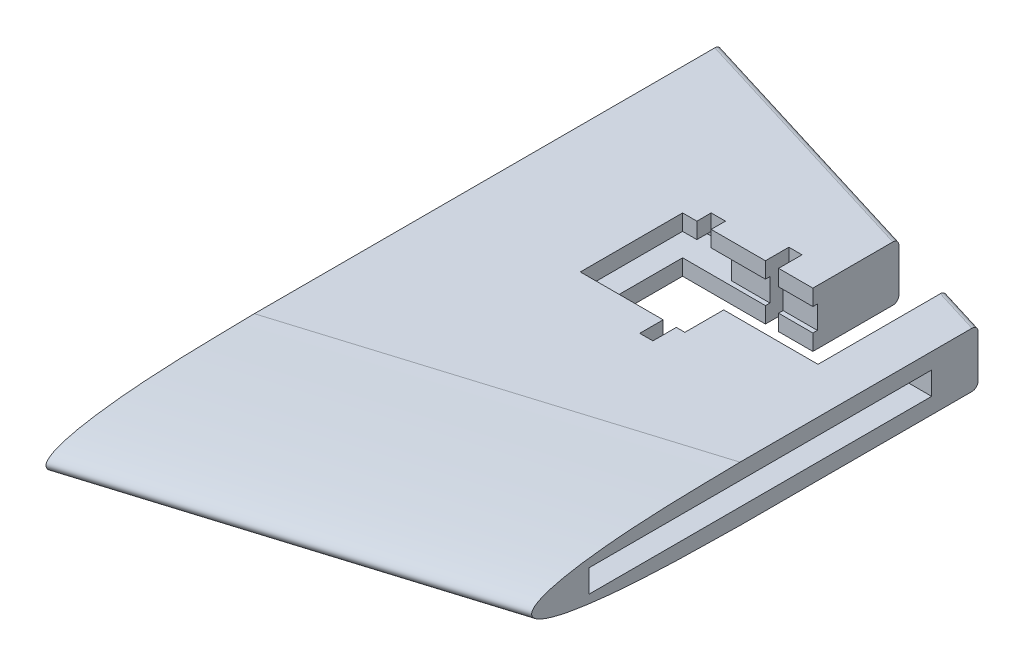
SolidWorks part; units mm, degrees
material "ABS"
ref_plane "Front Plane" through (0, 0, 0) normal (0, 0, 1) x (1, 0, 0)
ref_plane "Top Plane" through (0, 0, 0) normal (0, 1, 0) x (1, 0, 0)
ref_plane "Right Plane" through (0, 0, 0) normal (1, 0, 0) x (0, 0, -1)
sketch "Sketch2" plane through (0, 0, 0) normal (1, 0, 0) x (0, 0, -1)
  line L0 (10, -10.5) -> (10, 10.5)
  line L1 (20, -10.5) -> (20, 10.5)
  line L2 (30, -10.5) -> (30, 10.5)
  line L3 (40, -10.5) -> (40, 10.5)
  line L4 (50, -10.5) -> (50, 10.5)
  line L5 (60, -10.5) -> (60, 10.5)
  line L6 (70, -10.5) -> (70, 10.5)
  line L7 (80, -10.5) -> (80, 10.5)
  line L8 (90, -10.5) -> (90, 10.5)
  line L9 (100, -10.5) -> (100, 10.5)
  line L10 (110, -10.5) -> (110, 10.5)
  line L11 (120, -10.5) -> (120, 10.5)
  line L12 (130, -10.5) -> (130, 10.5)
  line L13 (140, -10.5) -> (140, 10.5)
  line L14 (150, -10.5) -> (150, 10.5)
  line L15 (-4.5, 10) -> (154.5, 10)
  line L16 (-4.5, -10) -> (154.5, -10)
  line L17 (150, 0.13) -> (149.77, 0.15)
  line L18 (149.77, 0.15) -> (149.08, 0.21)
  line L19 (149.08, 0.21) -> (147.93, 0.32)
  line L20 (147.93, 0.32) -> (146.33, 0.46)
  line L21 (146.33, 0.46) -> (144.29, 0.65)
  line L22 (144.29, 0.65) -> (141.83, 0.87)
  line L23 (141.83, 0.87) -> (138.95, 1.11)
  line L24 (138.95, 1.11) -> (135.68, 1.39)
  line L25 (135.68, 1.39) -> (132.03, 1.69)
  line L26 (132.03, 1.69) -> (128.03, 2.01)
  line L27 (128.03, 2.01) -> (123.71, 2.35)
  line L28 (123.71, 2.35) -> (119.08, 2.69)
  line L29 (119.08, 2.69) -> (114.19, 3.04)
  line L30 (114.19, 3.04) -> (109.05, 3.4)
  line L31 (109.05, 3.4) -> (103.7, 3.75)
  line L32 (103.7, 3.75) -> (98.18, 4.09)
  line L33 (98.18, 4.09) -> (92.51, 4.42)
  line L34 (92.51, 4.42) -> (86.73, 4.74)
  line L35 (86.73, 4.74) -> (80.88, 5.03)
  line L36 (80.88, 5.03) -> (75, 5.29)
  line L37 (75, 5.29) -> (69.12, 5.52)
  line L38 (69.12, 5.52) -> (63.27, 5.71)
  line L39 (63.27, 5.71) -> (57.49, 5.86)
  line L40 (57.49, 5.86) -> (51.82, 5.96)
  line L41 (51.82, 5.96) -> (46.3, 6)
  line L42 (46.3, 6) -> (40.95, 5.98)
  line L43 (40.95, 5.98) -> (35.81, 5.91)
  line L44 (35.81, 5.91) -> (30.92, 5.77)
  line L45 (30.92, 5.77) -> (26.29, 5.57)
  line L46 (26.29, 5.57) -> (21.97, 5.31)
  line L47 (21.97, 5.31) -> (17.97, 4.99)
  line L48 (17.97, 4.99) -> (14.32, 4.6)
  line L49 (14.32, 4.6) -> (11.05, 4.17)
  line L50 (11.05, 4.17) -> (8.17, 3.69)
  line L51 (8.17, 3.69) -> (5.71, 3.16)
  line L52 (5.71, 3.16) -> (3.67, 2.59)
  line L53 (3.67, 2.59) -> (2.07, 1.99)
  line L54 (2.07, 1.99) -> (0.92, 1.35)
  line L55 (0.92, 1.35) -> (0.23, 0.69)
  line L56 (0.23, 0.69) -> (0, 0)
  line L57 (0, 0) -> (0.23, -0.69)
  line L58 (0.23, -0.69) -> (0.92, -1.35)
  line L59 (0.92, -1.35) -> (2.07, -1.99)
  line L60 (2.07, -1.99) -> (3.67, -2.59)
  line L61 (3.67, -2.59) -> (5.71, -3.16)
  line L62 (5.71, -3.16) -> (8.17, -3.69)
  line L63 (8.17, -3.69) -> (11.05, -4.17)
  line L64 (11.05, -4.17) -> (14.32, -4.6)
  line L65 (14.32, -4.6) -> (17.97, -4.99)
  line L66 (17.97, -4.99) -> (21.97, -5.31)
  line L67 (21.97, -5.31) -> (26.29, -5.57)
  line L68 (26.29, -5.57) -> (30.92, -5.77)
  line L69 (30.92, -5.77) -> (35.81, -5.91)
  line L70 (35.81, -5.91) -> (40.95, -5.98)
  line L71 (40.95, -5.98) -> (46.3, -6)
  line L72 (46.3, -6) -> (51.82, -5.96)
  line L73 (51.82, -5.96) -> (57.49, -5.86)
  line L74 (57.49, -5.86) -> (63.27, -5.71)
  line L75 (63.27, -5.71) -> (69.12, -5.52)
  line L76 (69.12, -5.52) -> (75, -5.29)
  line L77 (75, -5.29) -> (80.88, -5.03)
  line L78 (80.88, -5.03) -> (86.73, -4.74)
  line L79 (86.73, -4.74) -> (92.51, -4.42)
  line L80 (92.51, -4.42) -> (98.18, -4.09)
  line L81 (98.18, -4.09) -> (103.7, -3.75)
  line L82 (103.7, -3.75) -> (109.05, -3.4)
  line L83 (109.05, -3.4) -> (114.19, -3.04)
  line L84 (114.19, -3.04) -> (119.08, -2.69)
  line L85 (119.08, -2.69) -> (123.71, -2.35)
  line L86 (123.71, -2.35) -> (128.03, -2.01)
  line L87 (128.03, -2.01) -> (132.03, -1.69)
  line L88 (132.03, -1.69) -> (135.68, -1.39)
  line L89 (135.68, -1.39) -> (138.95, -1.11)
  line L90 (138.95, -1.11) -> (141.83, -0.87)
  line L91 (141.83, -0.87) -> (144.29, -0.65)
  line L92 (144.29, -0.65) -> (146.33, -0.46)
  line L93 (146.33, -0.46) -> (147.93, -0.32)
  line L94 (147.93, -0.32) -> (149.08, -0.21)
  line L95 (149.08, -0.21) -> (149.77, -0.15)
  line L96 (149.77, -0.15) -> (150, -0.13)
  line L97 (0, 0) -> (150, 0)
  line L98 (-4.5, 0) -> (154.5, 0)
  line L99 (0, -10.5) -> (0, 10.5)
  line L100 (-2.7943, -13.5) -> (-2.7943, -11.5673)
  line L101 (-2.7943, -11.5673) -> (-2.532, -11.5673)
  line L102 (-2.532, -11.5673) -> (-1.5168, -13.0847)
  line L103 (-1.5168, -13.0847) -> (-1.5168, -11.5673)
  line L104 (-1.5168, -11.5673) -> (-1.2716, -11.5673)
  line L105 (-1.2716, -11.5673) -> (-1.2716, -13.5)
  line L106 (-1.2716, -13.5) -> (-1.534, -13.5)
  line L107 (-1.534, -13.5) -> (-2.5491, -11.9812)
  line L108 (-2.5491, -11.9812) -> (-2.5491, -13.5)
  line L109 (-2.5491, -13.5) -> (-2.7943, -13.5)
  line L110 (0.0415, -13.3273) -> (-0.213, -13.4855)
  line L111 (-0.213, -13.4855) -> (-0.474, -13.5316)
  line L112 (-0.474, -13.5316) -> (-0.8287, -13.4196)
  line L113 (-0.8287, -13.4196) -> (-0.9526, -13.1309)
  line L114 (-0.9526, -13.1309) -> (-0.9064, -12.9437)
  line L115 (-0.9064, -12.9437) -> (-0.7838, -12.8065)
  line L116 (-0.7838, -12.8065) -> (-0.6125, -12.7288)
  line L117 (-0.6125, -12.7288) -> (-0.4015, -12.6932)
  line L118 (-0.4015, -12.6932) -> (0.0217, -12.6114)
  line L119 (0.0217, -12.6114) -> (0.023, -12.5495)
  line L120 (0.023, -12.5495) -> (-0.0442, -12.3451)
  line L121 (-0.0442, -12.3451) -> (-0.3145, -12.2647)
  line L122 (-0.3145, -12.2647) -> (-0.5624, -12.324)
  line L123 (-0.5624, -12.324) -> (-0.6797, -12.531)
  line L124 (-0.6797, -12.531) -> (-0.9117, -12.4994)
  line L125 (-0.9117, -12.4994) -> (-0.8076, -12.2594)
  line L126 (-0.8076, -12.2594) -> (-0.5979, -12.1184)
  line L127 (-0.5979, -12.1184) -> (-0.2802, -12.0683)
  line L128 (-0.2802, -12.0683) -> (0.0111, -12.1104)
  line L129 (0.0111, -12.1104) -> (0.1759, -12.2172)
  line L130 (0.1759, -12.2172) -> (0.2498, -12.3781)
  line L131 (0.2498, -12.3781) -> (0.2616, -12.5969)
  line L132 (0.2616, -12.5969) -> (0.2616, -12.9133)
  line L133 (0.2616, -12.9133) -> (0.2761, -13.3326)
  line L134 (0.2761, -13.3326) -> (0.3368, -13.5)
  line L135 (0.3368, -13.5) -> (0.0889, -13.5)
  line L136 (0.0889, -13.5) -> (0.0415, -13.3273)
  line L137 (0.0217, -12.7973) -> (-0.3659, -12.887)
  line L138 (-0.3659, -12.887) -> (-0.5729, -12.9344)
  line L139 (-0.5729, -12.9344) -> (-0.6665, -13.0122)
  line L140 (-0.6665, -13.0122) -> (-0.6995, -13.1243)
  line L141 (-0.6995, -13.1243) -> (-0.6283, -13.2825)
  line L142 (-0.6283, -13.2825) -> (-0.4173, -13.3458)
  line L143 (-0.4173, -13.3458) -> (-0.1734, -13.2864)
  line L144 (-0.1734, -13.2864) -> (-0.0166, -13.1216)
  line L145 (-0.0166, -13.1216) -> (0.0217, -12.8843)
  line L146 (0.0217, -12.8843) -> (0.0217, -12.7973)
  line L147 (0.6294, -13.5) -> (0.6294, -12.0999)
  line L148 (0.6294, -12.0999) -> (0.8417, -12.0999)
  line L149 (0.8417, -12.0999) -> (0.8417, -12.2963)
  line L150 (0.8417, -12.2963) -> (1.017, -12.1315)
  line L151 (1.017, -12.1315) -> (1.2662, -12.0683)
  line L152 (1.2662, -12.0683) -> (1.5207, -12.1329)
  line L153 (1.5207, -12.1329) -> (1.6617, -12.3135)
  line L154 (1.6617, -12.3135) -> (2.0941, -12.0683)
  line L155 (2.0941, -12.0683) -> (2.4145, -12.1843)
  line L156 (2.4145, -12.1843) -> (2.5266, -12.5389)
  line L157 (2.5266, -12.5389) -> (2.5266, -13.5)
  line L158 (2.5266, -13.5) -> (2.2906, -13.5)
  line L159 (2.2906, -13.5) -> (2.2906, -12.618)
  line L160 (2.2906, -12.618) -> (2.2668, -12.4137)
  line L161 (2.2668, -12.4137) -> (2.1838, -12.3122)
  line L162 (2.1838, -12.3122) -> (2.0414, -12.2739)
  line L163 (2.0414, -12.2739) -> (1.7962, -12.3728)
  line L164 (1.7962, -12.3728) -> (1.6986, -12.6866)
  line L165 (1.6986, -12.6866) -> (1.6986, -13.5)
  line L166 (1.6986, -13.5) -> (1.4613, -13.5)
  line L167 (1.4613, -13.5) -> (1.4613, -12.5903)
  line L168 (1.4613, -12.5903) -> (1.4033, -12.353)
  line L169 (1.4033, -12.353) -> (1.2135, -12.2739)
  line L170 (1.2135, -12.2739) -> (1.0276, -12.3267)
  line L171 (1.0276, -12.3267) -> (0.905, -12.4809)
  line L172 (0.905, -12.4809) -> (0.8667, -12.7736)
  line L173 (0.8667, -12.7736) -> (0.8667, -13.5)
  line L174 (0.8667, -13.5) -> (0.6294, -13.5)
  line L175 (3.837, -13.0491) -> (4.0822, -13.0794)
  line L176 (4.0822, -13.0794) -> (3.8673, -13.413)
  line L177 (3.8673, -13.413) -> (3.4666, -13.5316)
  line L178 (3.4666, -13.5316) -> (2.9788, -13.3431)
  line L179 (2.9788, -13.3431) -> (2.7995, -12.8118)
  line L180 (2.7995, -12.8118) -> (2.9814, -12.2634)
  line L181 (2.9814, -12.2634) -> (3.4534, -12.0683)
  line L182 (3.4534, -12.0683) -> (3.9122, -12.2594)
  line L183 (3.9122, -12.2594) -> (4.0901, -12.7973)
  line L184 (4.0901, -12.7973) -> (4.0888, -12.8606)
  line L185 (4.0888, -12.8606) -> (3.0447, -12.8606)
  line L186 (3.0447, -12.8606) -> (3.1752, -13.2139)
  line L187 (3.1752, -13.2139) -> (3.4679, -13.3365)
  line L188 (3.4679, -13.3365) -> (3.6907, -13.268)
  line L189 (3.6907, -13.268) -> (3.837, -13.0491)
  line L190 (3.0579, -12.6655) -> (3.8396, -12.6655)
  line L191 (3.8396, -12.6655) -> (3.75, -12.4005)
  line L192 (3.75, -12.4005) -> (3.456, -12.2634)
  line L193 (3.456, -12.2634) -> (3.1805, -12.3728)
  line L194 (3.1805, -12.3728) -> (3.0579, -12.6655)
  line L195 (6.3788, -12.3636) -> (5.1026, -12.3636)
  line L196 (5.1026, -12.3636) -> (5.1026, -12.1421)
  line L197 (5.1026, -12.1421) -> (6.3788, -12.1421)
  line L198 (6.3788, -12.1421) -> (6.3788, -12.3636)
  line L199 (6.3788, -12.9502) -> (5.1026, -12.9502)
  line L200 (5.1026, -12.9502) -> (5.1026, -12.7288)
  line L201 (5.1026, -12.7288) -> (6.3788, -12.7288)
  line L202 (6.3788, -12.7288) -> (6.3788, -12.9502)
  line L203 (7.4849, -13.5) -> (7.4849, -11.5673)
  line L204 (7.4849, -11.5673) -> (7.7473, -11.5673)
  line L205 (7.7473, -11.5673) -> (8.7624, -13.0847)
  line L206 (8.7624, -13.0847) -> (8.7624, -11.5673)
  line L207 (8.7624, -11.5673) -> (9.0076, -11.5673)
  line L208 (9.0076, -11.5673) -> (9.0076, -13.5)
  line L209 (9.0076, -13.5) -> (8.7453, -13.5)
  line L210 (8.7453, -13.5) -> (7.7301, -11.9812)
  line L211 (7.7301, -11.9812) -> (7.7301, -13.5)
  line L212 (7.7301, -13.5) -> (7.4849, -13.5)
  line L213 (9.2251, -13.5) -> (9.9674, -11.5673)
  line L214 (9.9674, -11.5673) -> (10.2429, -11.5673)
  line L215 (10.2429, -11.5673) -> (11.0339, -13.5)
  line L216 (11.0339, -13.5) -> (10.7426, -13.5)
  line L217 (10.7426, -13.5) -> (10.5171, -12.9146)
  line L218 (10.5171, -12.9146) -> (9.709, -12.9146)
  line L219 (9.709, -12.9146) -> (9.4967, -13.5)
  line L220 (9.4967, -13.5) -> (9.2251, -13.5)
  line L221 (9.7828, -12.7063) -> (10.438, -12.7063)
  line L222 (10.438, -12.7063) -> (10.2363, -12.1711)
  line L223 (10.2363, -12.1711) -> (10.0992, -11.7703)
  line L224 (10.0992, -11.7703) -> (9.9951, -12.1395)
  line L225 (9.9951, -12.1395) -> (9.7828, -12.7063)
  line L226 (12.6173, -12.8224) -> (12.873, -12.887)
  line L227 (12.873, -12.887) -> (12.583, -13.3682)
  line L228 (12.583, -13.3682) -> (12.0728, -13.533)
  line L229 (12.0728, -13.533) -> (11.5639, -13.4064)
  line L230 (11.5639, -13.4064) -> (11.266, -13.0373)
  line L231 (11.266, -13.0373) -> (11.1645, -12.5191)
  line L232 (11.1645, -12.5191) -> (11.2792, -11.9931)
  line L233 (11.2792, -11.9931) -> (11.6074, -11.6517)
  line L234 (11.6074, -11.6517) -> (12.0768, -11.5343)
  line L235 (12.0768, -11.5343) -> (12.5646, -11.682)
  line L236 (12.5646, -11.682) -> (12.8401, -12.0973)
  line L237 (12.8401, -12.0973) -> (12.5883, -12.1566)
  line L238 (12.5883, -12.1566) -> (12.3932, -11.8494)
  line L239 (12.3932, -11.8494) -> (12.0715, -11.7532)
  line L240 (12.0715, -11.7532) -> (11.6984, -11.86)
  line L241 (11.6984, -11.86) -> (11.4888, -12.1474)
  line L242 (11.4888, -12.1474) -> (11.4281, -12.5178)
  line L243 (11.4281, -12.5178) -> (11.4993, -12.9489)
  line L244 (11.4993, -12.9489) -> (11.7234, -13.2231)
  line L245 (11.7234, -13.2231) -> (12.0517, -13.3141)
  line L246 (12.0517, -13.3141) -> (12.4156, -13.1902)
  line L247 (12.4156, -13.1902) -> (12.6173, -12.8224)
  line L248 (12.9759, -13.5) -> (13.7181, -11.5673)
  line L249 (13.7181, -11.5673) -> (13.9937, -11.5673)
  line L250 (13.9937, -11.5673) -> (14.7847, -13.5)
  line L251 (14.7847, -13.5) -> (14.4933, -13.5)
  line L252 (14.4933, -13.5) -> (14.2679, -12.9146)
  line L253 (14.2679, -12.9146) -> (13.4597, -12.9146)
  line L254 (13.4597, -12.9146) -> (13.2475, -13.5)
  line L255 (13.2475, -13.5) -> (12.9759, -13.5)
  line L256 (13.5335, -12.7063) -> (14.1888, -12.7063)
  line L257 (14.1888, -12.7063) -> (13.9871, -12.1711)
  line L258 (13.9871, -12.1711) -> (13.8499, -11.7703)
  line L259 (13.8499, -11.7703) -> (13.7458, -12.1395)
  line L260 (13.7458, -12.1395) -> (13.5335, -12.7063)
  line L261 (15.4939, -12.5468) -> (15.5638, -11.9958)
  line L262 (15.5638, -11.9958) -> (15.7734, -11.6728)
  line L263 (15.7734, -11.6728) -> (16.1241, -11.5594)
  line L264 (16.1241, -11.5594) -> (16.397, -11.6227)
  line L265 (16.397, -11.6227) -> (16.5908, -11.8033)
  line L266 (16.5908, -11.8033) -> (16.7108, -12.0907)
  line L267 (16.7108, -12.0907) -> (16.7543, -12.5468)
  line L268 (16.7543, -12.5468) -> (16.6844, -13.0966)
  line L269 (16.6844, -13.0966) -> (16.4748, -13.4196)
  line L270 (16.4748, -13.4196) -> (16.1241, -13.533)
  line L271 (16.1241, -13.533) -> (15.6851, -13.3326)
  line L272 (15.6851, -13.3326) -> (15.4939, -12.5468)
  line L273 (15.7378, -12.5468) -> (15.8486, -13.181)
  line L274 (15.8486, -13.181) -> (16.1241, -13.3378)
  line L275 (16.1241, -13.3378) -> (16.3983, -13.1796)
  line L276 (16.3983, -13.1796) -> (16.5104, -12.5468)
  line L277 (16.5104, -12.5468) -> (16.3983, -11.9127)
  line L278 (16.3983, -11.9127) -> (16.1215, -11.7558)
  line L279 (16.1215, -11.7558) -> (15.8605, -11.8942)
  line L280 (15.8605, -11.8942) -> (15.7378, -12.5468)
  line L281 (16.9956, -12.5468) -> (17.0654, -11.9958)
  line L282 (17.0654, -11.9958) -> (17.275, -11.6728)
  line L283 (17.275, -11.6728) -> (17.6257, -11.5594)
  line L284 (17.6257, -11.5594) -> (17.8986, -11.6227)
  line L285 (17.8986, -11.6227) -> (18.0924, -11.8033)
  line L286 (18.0924, -11.8033) -> (18.2124, -12.0907)
  line L287 (18.2124, -12.0907) -> (18.2559, -12.5468)
  line L288 (18.2559, -12.5468) -> (18.186, -13.0966)
  line L289 (18.186, -13.0966) -> (17.9764, -13.4196)
  line L290 (17.9764, -13.4196) -> (17.6257, -13.533)
  line L291 (17.6257, -13.533) -> (17.1867, -13.3326)
  line L292 (17.1867, -13.3326) -> (16.9956, -12.5468)
  line L293 (17.2395, -12.5468) -> (17.3502, -13.181)
  line L294 (17.3502, -13.181) -> (17.6257, -13.3378)
  line L295 (17.6257, -13.3378) -> (17.9, -13.1796)
  line L296 (17.9, -13.1796) -> (18.012, -12.5468)
  line L297 (18.012, -12.5468) -> (17.9, -11.9127)
  line L298 (17.9, -11.9127) -> (17.6231, -11.7558)
  line L299 (17.6231, -11.7558) -> (17.3621, -11.8942)
  line L300 (17.3621, -11.8942) -> (17.2395, -12.5468)
  line L301 (18.4972, -12.5468) -> (18.567, -11.9958)
  line L302 (18.567, -11.9958) -> (18.7767, -11.6728)
  line L303 (18.7767, -11.6728) -> (19.1273, -11.5594)
  line L304 (19.1273, -11.5594) -> (19.4002, -11.6227)
  line L305 (19.4002, -11.6227) -> (19.594, -11.8033)
  line L306 (19.594, -11.8033) -> (19.714, -12.0907)
  line L307 (19.714, -12.0907) -> (19.7575, -12.5468)
  line L308 (19.7575, -12.5468) -> (19.6876, -13.0966)
  line L309 (19.6876, -13.0966) -> (19.478, -13.4196)
  line L310 (19.478, -13.4196) -> (19.1273, -13.533)
  line L311 (19.1273, -13.533) -> (18.6883, -13.3326)
  line L312 (18.6883, -13.3326) -> (18.4972, -12.5468)
  line L313 (18.7411, -12.5468) -> (18.8518, -13.181)
  line L314 (18.8518, -13.181) -> (19.1273, -13.3378)
  line L315 (19.1273, -13.3378) -> (19.4016, -13.1796)
  line L316 (19.4016, -13.1796) -> (19.5136, -12.5468)
  line L317 (19.5136, -12.5468) -> (19.4016, -11.9127)
  line L318 (19.4016, -11.9127) -> (19.1247, -11.7558)
  line L319 (19.1247, -11.7558) -> (18.8637, -11.8942)
  line L320 (18.8637, -11.8942) -> (18.7411, -12.5468)
  line L321 (20.364, -12.4519) -> (20.1451, -12.2977)
  line L322 (20.1451, -12.2977) -> (20.0739, -12.0577)
  line L323 (20.0739, -12.0577) -> (20.2255, -11.7031)
  line L324 (20.2255, -11.7031) -> (20.629, -11.5594)
  line L325 (20.629, -11.5594) -> (21.0363, -11.707)
  line L326 (21.0363, -11.707) -> (21.1906, -12.0643)
  line L327 (21.1906, -12.0643) -> (21.1194, -12.299)
  line L328 (21.1194, -12.299) -> (20.9058, -12.4519)
  line L329 (20.9058, -12.4519) -> (21.1761, -12.6391)
  line L330 (21.1761, -12.6391) -> (21.2697, -12.9476)
  line L331 (21.2697, -12.9476) -> (21.0943, -13.3642)
  line L332 (21.0943, -13.3642) -> (20.6329, -13.533)
  line L333 (20.6329, -13.533) -> (20.1715, -13.3642)
  line L334 (20.1715, -13.3642) -> (19.9961, -12.941)
  line L335 (19.9961, -12.941) -> (20.0911, -12.6259)
  line L336 (20.0911, -12.6259) -> (20.364, -12.4519)
  line L337 (20.3165, -12.0498) -> (20.4048, -12.2739)
  line L338 (20.4048, -12.2739) -> (20.6342, -12.3609)
  line L339 (20.6342, -12.3609) -> (20.8584, -12.2752)
  line L340 (20.8584, -12.2752) -> (20.9467, -12.063)
  line L341 (20.9467, -12.063) -> (20.8557, -11.8441)
  line L342 (20.8557, -11.8441) -> (20.6316, -11.7545)
  line L343 (20.6316, -11.7545) -> (20.4062, -11.8415)
  line L344 (20.4062, -11.8415) -> (20.3165, -12.0498)
  line L345 (20.24, -12.9423) -> (20.2875, -13.1388)
  line L346 (20.2875, -13.1388) -> (20.4312, -13.2864)
  line L347 (20.4312, -13.2864) -> (20.6355, -13.3378)
  line L348 (20.6355, -13.3378) -> (20.9164, -13.2284)
  line L349 (20.9164, -13.2284) -> (21.0271, -12.9502)
  line L350 (21.0271, -12.9502) -> (20.9124, -12.6668)
  line L351 (20.9124, -12.6668) -> (20.6276, -12.5547)
  line L352 (20.6276, -12.5547) -> (20.3495, -12.6655)
  line L353 (20.3495, -12.6655) -> (20.24, -12.9423)
  line L354 (21.9855, -13.5) -> (22.7278, -11.5673)
  line L355 (22.7278, -11.5673) -> (23.0033, -11.5673)
  line L356 (23.0033, -11.5673) -> (23.7943, -13.5)
  line L357 (23.7943, -13.5) -> (23.503, -13.5)
  line L358 (23.503, -13.5) -> (23.2775, -12.9146)
  line L359 (23.2775, -12.9146) -> (22.4694, -12.9146)
  line L360 (22.4694, -12.9146) -> (22.2571, -13.5)
  line L361 (22.2571, -13.5) -> (21.9855, -13.5)
  line L362 (22.5432, -12.7063) -> (23.1984, -12.7063)
  line L363 (23.1984, -12.7063) -> (22.9967, -12.1711)
  line L364 (22.9967, -12.1711) -> (22.8596, -11.7703)
  line L365 (22.8596, -11.7703) -> (22.7555, -12.1395)
  line L366 (22.7555, -12.1395) -> (22.5432, -12.7063)
  line L367 (23.9697, -11.8402) -> (23.9697, -11.5673)
  line L368 (23.9697, -11.5673) -> (24.207, -11.5673)
  line L369 (24.207, -11.5673) -> (24.207, -11.8402)
  line L370 (24.207, -11.8402) -> (23.9697, -11.8402)
  line L371 (23.9697, -13.5) -> (23.9697, -12.0999)
  line L372 (23.9697, -12.0999) -> (24.207, -12.0999)
  line L373 (24.207, -12.0999) -> (24.207, -13.5)
  line L374 (24.207, -13.5) -> (23.9697, -13.5)
  line L375 (24.5656, -13.5) -> (24.5656, -12.0999)
  line L376 (24.5656, -12.0999) -> (24.7792, -12.0999)
  line L377 (24.7792, -12.0999) -> (24.7792, -12.3122)
  line L378 (24.7792, -12.3122) -> (24.9294, -12.1157)
  line L379 (24.9294, -12.1157) -> (25.0824, -12.0683)
  line L380 (25.0824, -12.0683) -> (25.3263, -12.1447)
  line L381 (25.3263, -12.1447) -> (25.2445, -12.3649)
  line L382 (25.2445, -12.3649) -> (25.0705, -12.3135)
  line L383 (25.0705, -12.3135) -> (24.9308, -12.3609)
  line L384 (24.9308, -12.3609) -> (24.8424, -12.4901)
  line L385 (24.8424, -12.4901) -> (24.8029, -12.767)
  line L386 (24.8029, -12.767) -> (24.8029, -13.5)
  line L387 (24.8029, -13.5) -> (24.5656, -13.5)
  line L388 (25.524, -13.5) -> (25.524, -12.2845)
  line L389 (25.524, -12.2845) -> (25.3144, -12.2845)
  line L390 (25.3144, -12.2845) -> (25.3144, -12.0999)
  line L391 (25.3144, -12.0999) -> (25.524, -12.0999)
  line L392 (25.524, -12.0999) -> (25.524, -11.9509)
  line L393 (25.524, -11.9509) -> (25.5491, -11.7413)
  line L394 (25.5491, -11.7413) -> (25.669, -11.5923)
  line L395 (25.669, -11.5923) -> (25.9116, -11.5343)
  line L396 (25.9116, -11.5343) -> (26.1331, -11.5581)
  line L397 (26.1331, -11.5581) -> (26.0975, -11.765)
  line L398 (26.0975, -11.765) -> (25.9578, -11.7519)
  line L399 (25.9578, -11.7519) -> (25.8048, -11.798)
  line L400 (25.8048, -11.798) -> (25.76, -11.9707)
  line L401 (25.76, -11.9707) -> (25.76, -12.0999)
  line L402 (25.76, -12.0999) -> (26.0329, -12.0999)
  line L403 (26.0329, -12.0999) -> (26.0329, -12.2845)
  line L404 (26.0329, -12.2845) -> (25.76, -12.2845)
  line L405 (25.76, -12.2845) -> (25.76, -13.5)
  line L406 (25.76, -13.5) -> (25.524, -13.5)
  line L407 (26.1291, -12.8) -> (26.3454, -12.2238)
  line L408 (26.3454, -12.2238) -> (26.7857, -12.0683)
  line L409 (26.7857, -12.0683) -> (27.2577, -12.2581)
  line L410 (27.2577, -12.2581) -> (27.4409, -12.7802)
  line L411 (27.4409, -12.7802) -> (27.3592, -13.206)
  line L412 (27.3592, -13.206) -> (27.1232, -13.4459)
  line L413 (27.1232, -13.4459) -> (26.7857, -13.5316)
  line L414 (26.7857, -13.5316) -> (26.3098, -13.3431)
  line L415 (26.3098, -13.3431) -> (26.1291, -12.8)
  line L416 (26.373, -12.8) -> (26.4904, -13.2034)
  line L417 (26.4904, -13.2034) -> (26.7857, -13.3365)
  line L418 (26.7857, -13.3365) -> (27.0797, -13.2021)
  line L419 (27.0797, -13.2021) -> (27.197, -12.792)
  line L420 (27.197, -12.792) -> (27.0784, -12.3992)
  line L421 (27.0784, -12.3992) -> (26.7857, -12.2647)
  line L422 (26.7857, -12.2647) -> (26.4904, -12.3979)
  line L423 (26.4904, -12.3979) -> (26.373, -12.8)
  line L424 (27.7204, -11.8402) -> (27.7204, -11.5673)
  line L425 (27.7204, -11.5673) -> (27.9577, -11.5673)
  line L426 (27.9577, -11.5673) -> (27.9577, -11.8402)
  line L427 (27.9577, -11.8402) -> (27.7204, -11.8402)
  line L428 (27.7204, -13.5) -> (27.7204, -12.0999)
  line L429 (27.7204, -12.0999) -> (27.9577, -12.0999)
  line L430 (27.9577, -12.0999) -> (27.9577, -13.5)
  line L431 (27.9577, -13.5) -> (27.7204, -13.5)
  line L432 (28.3137, -13.5) -> (28.3137, -11.5673)
  line L433 (28.3137, -11.5673) -> (28.551, -11.5673)
  line L434 (28.551, -11.5673) -> (28.551, -13.5)
  line L435 (28.551, -13.5) -> (28.3137, -13.5)
  line L436 (29.6914, -13.5) -> (29.6914, -11.5673)
  line L437 (29.6914, -11.5673) -> (30.0763, -11.5673)
  line L438 (30.0763, -11.5673) -> (30.5338, -12.9357)
  line L439 (30.5338, -12.9357) -> (30.6261, -13.2218)
  line L440 (30.6261, -13.2218) -> (30.7289, -12.912)
  line L441 (30.7289, -12.912) -> (31.1916, -11.5673)
  line L442 (31.1916, -11.5673) -> (31.5357, -11.5673)
  line L443 (31.5357, -11.5673) -> (31.5357, -13.5)
  line L444 (31.5357, -13.5) -> (31.2892, -13.5)
  line L445 (31.2892, -13.5) -> (31.2892, -11.8824)
  line L446 (31.2892, -11.8824) -> (30.7276, -13.5)
  line L447 (30.7276, -13.5) -> (30.4969, -13.5)
  line L448 (30.4969, -13.5) -> (29.9379, -11.8547)
  line L449 (29.9379, -11.8547) -> (29.9379, -13.5)
  line L450 (29.9379, -13.5) -> (29.6914, -13.5)
  line L451 (33.1666, -12.3636) -> (31.8904, -12.3636)
  line L452 (31.8904, -12.3636) -> (31.8904, -12.1421)
  line L453 (31.8904, -12.1421) -> (33.1666, -12.1421)
  line L454 (33.1666, -12.1421) -> (33.1666, -12.3636)
  line L455 (33.1666, -12.9502) -> (31.8904, -12.9502)
  line L456 (31.8904, -12.9502) -> (31.8904, -12.7288)
  line L457 (31.8904, -12.7288) -> (33.1666, -12.7288)
  line L458 (33.1666, -12.7288) -> (33.1666, -12.9502)
  line L459 (33.4289, -12.5468) -> (33.4988, -11.9958)
  line L460 (33.4988, -11.9958) -> (33.7084, -11.6728)
  line L461 (33.7084, -11.6728) -> (34.0591, -11.5594)
  line L462 (34.0591, -11.5594) -> (34.332, -11.6227)
  line L463 (34.332, -11.6227) -> (34.5258, -11.8033)
  line L464 (34.5258, -11.8033) -> (34.6457, -12.0907)
  line L465 (34.6457, -12.0907) -> (34.6892, -12.5468)
  line L466 (34.6892, -12.5468) -> (34.6194, -13.0966)
  line L467 (34.6194, -13.0966) -> (34.4098, -13.4196)
  line L468 (34.4098, -13.4196) -> (34.0591, -13.533)
  line L469 (34.0591, -13.533) -> (33.6201, -13.3326)
  line L470 (33.6201, -13.3326) -> (33.4289, -12.5468)
  line L471 (33.6728, -12.5468) -> (33.7835, -13.181)
  line L472 (33.7835, -13.181) -> (34.0591, -13.3378)
  line L473 (34.0591, -13.3378) -> (34.3333, -13.1796)
  line L474 (34.3333, -13.1796) -> (34.4454, -12.5468)
  line L475 (34.4454, -12.5468) -> (34.3333, -11.9127)
  line L476 (34.3333, -11.9127) -> (34.0564, -11.7558)
  line L477 (34.0564, -11.7558) -> (33.7954, -11.8942)
  line L478 (33.7954, -11.8942) -> (33.6728, -12.5468)
  line L479 (35.0637, -13.5) -> (35.0637, -13.2297)
  line L480 (35.0637, -13.2297) -> (35.3339, -13.2297)
  line L481 (35.3339, -13.2297) -> (35.3339, -13.5)
  line L482 (35.3339, -13.5) -> (35.0637, -13.5)
  line L483 (35.6807, -12.5468) -> (35.7505, -11.9958)
  line L484 (35.7505, -11.9958) -> (35.9602, -11.6728)
  line L485 (35.9602, -11.6728) -> (36.3108, -11.5594)
  line L486 (36.3108, -11.5594) -> (36.5837, -11.6227)
  line L487 (36.5837, -11.6227) -> (36.7775, -11.8033)
  line L488 (36.7775, -11.8033) -> (36.8975, -12.0907)
  line L489 (36.8975, -12.0907) -> (36.941, -12.5468)
  line L490 (36.941, -12.5468) -> (36.8711, -13.0966)
  line L491 (36.8711, -13.0966) -> (36.6615, -13.4196)
  line L492 (36.6615, -13.4196) -> (36.3108, -13.533)
  line L493 (36.3108, -13.533) -> (35.8718, -13.3326)
  line L494 (35.8718, -13.3326) -> (35.6807, -12.5468)
  line L495 (35.9246, -12.5468) -> (36.0353, -13.181)
  line L496 (36.0353, -13.181) -> (36.3108, -13.3378)
  line L497 (36.3108, -13.3378) -> (36.5851, -13.1796)
  line L498 (36.5851, -13.1796) -> (36.6971, -12.5468)
  line L499 (36.6971, -12.5468) -> (36.5851, -11.9127)
  line L500 (36.5851, -11.9127) -> (36.3082, -11.7558)
  line L501 (36.3082, -11.7558) -> (36.0472, -11.8942)
  line L502 (36.0472, -11.8942) -> (35.9246, -12.5468)
  line L503 (37.2271, -12.0313) -> (37.3312, -11.6793)
  line L504 (37.3312, -11.6793) -> (37.6331, -11.5343)
  line L505 (37.6331, -11.5343) -> (37.9337, -11.6648)
  line L506 (37.9337, -11.6648) -> (38.0537, -12.0458)
  line L507 (38.0537, -12.0458) -> (37.9324, -12.4242)
  line L508 (37.9324, -12.4242) -> (37.6358, -12.5561)
  line L509 (37.6358, -12.5561) -> (37.3431, -12.4255)
  line L510 (37.3431, -12.4255) -> (37.2271, -12.0313)
  line L511 (37.6397, -11.6978) -> (37.4921, -11.7743)
  line L512 (37.4921, -11.7743) -> (37.4341, -12.0551)
  line L513 (37.4341, -12.0551) -> (37.4934, -12.3174)
  line L514 (37.4934, -12.3174) -> (37.6397, -12.3926)
  line L515 (37.6397, -12.3926) -> (37.7874, -12.3161)
  line L516 (37.7874, -12.3161) -> (37.8467, -12.0366)
  line L517 (37.8467, -12.0366) -> (37.7874, -11.7743)
  line L518 (37.7874, -11.7743) -> (37.6397, -11.6978)
  line L519 (37.6411, -13.5712) -> (38.6984, -11.5343)
  line L520 (38.6984, -11.5343) -> (38.8909, -11.5343)
  line L521 (38.8909, -11.5343) -> (37.8375, -13.5712)
  line L522 (37.8375, -13.5712) -> (37.6411, -13.5712)
  line L523 (38.4769, -13.0465) -> (38.581, -12.6945)
  line L524 (38.581, -12.6945) -> (38.8843, -12.5495)
  line L525 (38.8843, -12.5495) -> (39.1849, -12.68)
  line L526 (39.1849, -12.68) -> (39.3048, -13.061)
  line L527 (39.3048, -13.061) -> (39.1835, -13.4394)
  line L528 (39.1835, -13.4394) -> (38.8856, -13.5712)
  line L529 (38.8856, -13.5712) -> (38.5929, -13.4407)
  line L530 (38.5929, -13.4407) -> (38.4769, -13.0465)
  line L531 (38.8909, -12.7129) -> (38.7419, -12.7894)
  line L532 (38.7419, -12.7894) -> (38.6839, -13.0702)
  line L533 (38.6839, -13.0702) -> (38.7432, -13.3312)
  line L534 (38.7432, -13.3312) -> (38.8895, -13.4077)
  line L535 (38.8895, -13.4077) -> (39.0385, -13.3312)
  line L536 (39.0385, -13.3312) -> (39.0979, -13.0518)
  line L537 (39.0979, -13.0518) -> (39.0385, -12.7894)
  line L538 (39.0385, -12.7894) -> (38.8909, -12.7129)
  line L539 (40.4294, -13.5) -> (40.4294, -11.5673)
  line L540 (40.4294, -11.5673) -> (41.1584, -11.5673)
  line L541 (41.1584, -11.5673) -> (41.4524, -11.5857)
  line L542 (41.4524, -11.5857) -> (41.6911, -11.6767)
  line L543 (41.6911, -11.6767) -> (41.8453, -11.8626)
  line L544 (41.8453, -11.8626) -> (41.9046, -12.1263)
  line L545 (41.9046, -12.1263) -> (41.7478, -12.5442)
  line L546 (41.7478, -12.5442) -> (41.1809, -12.7143)
  line L547 (41.1809, -12.7143) -> (40.6852, -12.7143)
  line L548 (40.6852, -12.7143) -> (40.6852, -13.5)
  line L549 (40.6852, -13.5) -> (40.4294, -13.5)
  line L550 (40.6852, -12.4862) -> (41.1848, -12.4862)
  line L551 (41.1848, -12.4862) -> (41.5368, -12.3939)
  line L552 (41.5368, -12.3939) -> (41.641, -12.1342)
  line L553 (41.641, -12.1342) -> (41.579, -11.9272)
  line L554 (41.579, -11.9272) -> (41.4182, -11.8125)
  line L555 (41.4182, -11.8125) -> (41.1795, -11.7954)
  line L556 (41.1795, -11.7954) -> (40.6851, -11.7954)
  line L557 (40.6851, -11.7954) -> (40.6852, -12.4862)
  line L558 (43.4484, -12.3636) -> (42.1723, -12.3636)
  line L559 (42.1723, -12.3636) -> (42.1723, -12.1421)
  line L560 (42.1723, -12.1421) -> (43.4484, -12.1421)
  line L561 (43.4484, -12.1421) -> (43.4484, -12.3636)
  line L562 (43.4484, -12.9502) -> (42.1723, -12.9502)
  line L563 (42.1723, -12.9502) -> (42.1723, -12.7288)
  line L564 (42.1723, -12.7288) -> (43.4484, -12.7288)
  line L565 (43.4484, -12.7288) -> (43.4484, -12.9502)
  line L566 (43.7108, -12.5468) -> (43.7807, -11.9958)
  line L567 (43.7807, -11.9958) -> (43.9903, -11.6728)
  line L568 (43.9903, -11.6728) -> (44.341, -11.5594)
  line L569 (44.341, -11.5594) -> (44.6139, -11.6227)
  line L570 (44.6139, -11.6227) -> (44.8077, -11.8033)
  line L571 (44.8077, -11.8033) -> (44.9276, -12.0907)
  line L572 (44.9276, -12.0907) -> (44.9711, -12.5468)
  line L573 (44.9711, -12.5468) -> (44.9013, -13.0966)
  line L574 (44.9013, -13.0966) -> (44.6916, -13.4196)
  line L575 (44.6916, -13.4196) -> (44.341, -13.533)
  line L576 (44.341, -13.533) -> (43.9019, -13.3326)
  line L577 (43.9019, -13.3326) -> (43.7108, -12.5468)
  line L578 (43.9547, -12.5468) -> (44.0654, -13.181)
  line L579 (44.0654, -13.181) -> (44.341, -13.3378)
  line L580 (44.341, -13.3378) -> (44.6152, -13.1796)
  line L581 (44.6152, -13.1796) -> (44.7272, -12.5468)
  line L582 (44.7272, -12.5468) -> (44.6152, -11.9127)
  line L583 (44.6152, -11.9127) -> (44.3383, -11.7558)
  line L584 (44.3383, -11.7558) -> (44.0773, -11.8942)
  line L585 (44.0773, -11.8942) -> (43.9547, -12.5468)
  line L586 (45.3456, -13.5) -> (45.3456, -13.2297)
  line L587 (45.3456, -13.2297) -> (45.6158, -13.2297)
  line L588 (45.6158, -13.2297) -> (45.6158, -13.5)
  line L589 (45.6158, -13.5) -> (45.3456, -13.5)
  line L590 (45.9625, -12.5468) -> (46.0324, -11.9958)
  line L591 (46.0324, -11.9958) -> (46.242, -11.6728)
  line L592 (46.242, -11.6728) -> (46.5927, -11.5594)
  line L593 (46.5927, -11.5594) -> (46.8656, -11.6227)
  line L594 (46.8656, -11.6227) -> (47.0594, -11.8033)
  line L595 (47.0594, -11.8033) -> (47.1794, -12.0907)
  line L596 (47.1794, -12.0907) -> (47.2229, -12.5468)
  line L597 (47.2229, -12.5468) -> (47.153, -13.0966)
  line L598 (47.153, -13.0966) -> (46.9434, -13.4196)
  line L599 (46.9434, -13.4196) -> (46.5927, -13.533)
  line L600 (46.5927, -13.533) -> (46.1537, -13.3326)
  line L601 (46.1537, -13.3326) -> (45.9625, -12.5468)
  line L602 (46.2064, -12.5468) -> (46.3172, -13.181)
  line L603 (46.3172, -13.181) -> (46.5927, -13.3378)
  line L604 (46.5927, -13.3378) -> (46.8669, -13.1796)
  line L605 (46.8669, -13.1796) -> (46.979, -12.5468)
  line L606 (46.979, -12.5468) -> (46.8669, -11.9127)
  line L607 (46.8669, -11.9127) -> (46.5901, -11.7558)
  line L608 (46.5901, -11.7558) -> (46.3291, -11.8942)
  line L609 (46.3291, -11.8942) -> (46.2064, -12.5468)
  line L610 (47.509, -12.0313) -> (47.6131, -11.6793)
  line L611 (47.6131, -11.6793) -> (47.915, -11.5343)
  line L612 (47.915, -11.5343) -> (48.2156, -11.6648)
  line L613 (48.2156, -11.6648) -> (48.3356, -12.0458)
  line L614 (48.3356, -12.0458) -> (48.2143, -12.4242)
  line L615 (48.2143, -12.4242) -> (47.9177, -12.5561)
  line L616 (47.9177, -12.5561) -> (47.625, -12.4255)
  line L617 (47.625, -12.4255) -> (47.509, -12.0313)
  line L618 (47.9216, -11.6978) -> (47.774, -11.7743)
  line L619 (47.774, -11.7743) -> (47.716, -12.0551)
  line L620 (47.716, -12.0551) -> (47.7753, -12.3174)
  line L621 (47.7753, -12.3174) -> (47.9216, -12.3926)
  line L622 (47.9216, -12.3926) -> (48.0693, -12.3161)
  line L623 (48.0693, -12.3161) -> (48.1286, -12.0366)
  line L624 (48.1286, -12.0366) -> (48.0693, -11.7743)
  line L625 (48.0693, -11.7743) -> (47.9216, -11.6978)
  line L626 (47.9229, -13.5712) -> (48.9803, -11.5343)
  line L627 (48.9803, -11.5343) -> (49.1728, -11.5343)
  line L628 (49.1728, -11.5343) -> (48.1194, -13.5712)
  line L629 (48.1194, -13.5712) -> (47.9229, -13.5712)
  line L630 (48.7588, -13.0465) -> (48.8629, -12.6945)
  line L631 (48.8629, -12.6945) -> (49.1662, -12.5495)
  line L632 (49.1662, -12.5495) -> (49.4667, -12.68)
  line L633 (49.4667, -12.68) -> (49.5867, -13.061)
  line L634 (49.5867, -13.061) -> (49.4654, -13.4394)
  line L635 (49.4654, -13.4394) -> (49.1675, -13.5712)
  line L636 (49.1675, -13.5712) -> (48.8748, -13.4407)
  line L637 (48.8748, -13.4407) -> (48.7588, -13.0465)
  line L638 (49.1728, -12.7129) -> (49.0238, -12.7894)
  line L639 (49.0238, -12.7894) -> (48.9658, -13.0702)
  line L640 (48.9658, -13.0702) -> (49.0251, -13.3312)
  line L641 (49.0251, -13.3312) -> (49.1714, -13.4077)
  line L642 (49.1714, -13.4077) -> (49.3204, -13.3312)
  line L643 (49.3204, -13.3312) -> (49.3797, -13.0518)
  line L644 (49.3797, -13.0518) -> (49.3204, -12.7894)
  line L645 (49.3204, -12.7894) -> (49.1728, -12.7129)
  line L646 (51.1543, -13.5) -> (51.1543, -11.7954)
  line L647 (51.1543, -11.7954) -> (50.5175, -11.7954)
  line L648 (50.5175, -11.7954) -> (50.5175, -11.5673)
  line L649 (50.5175, -11.5673) -> (52.0494, -11.5673)
  line L650 (52.0494, -11.5673) -> (52.0494, -11.7954)
  line L651 (52.0494, -11.7954) -> (51.41, -11.7954)
  line L652 (51.41, -11.7954) -> (51.41, -13.5)
  line L653 (51.41, -13.5) -> (51.1543, -13.5)
  line L654 (53.5299, -12.3636) -> (52.2538, -12.3636)
  line L655 (52.2538, -12.3636) -> (52.2538, -12.1421)
  line L656 (52.2538, -12.1421) -> (53.5299, -12.1421)
  line L657 (53.5299, -12.1421) -> (53.5299, -12.3636)
  line L658 (53.5299, -12.9502) -> (52.2538, -12.9502)
  line L659 (52.2538, -12.9502) -> (52.2538, -12.7288)
  line L660 (52.2538, -12.7288) -> (53.5299, -12.7288)
  line L661 (53.5299, -12.7288) -> (53.5299, -12.9502)
  line L662 (54.1575, -12.4519) -> (53.9386, -12.2977)
  line L663 (53.9386, -12.2977) -> (53.8674, -12.0577)
  line L664 (53.8674, -12.0577) -> (54.019, -11.7031)
  line L665 (54.019, -11.7031) -> (54.4225, -11.5594)
  line L666 (54.4225, -11.5594) -> (54.8298, -11.707)
  line L667 (54.8298, -11.707) -> (54.9841, -12.0643)
  line L668 (54.9841, -12.0643) -> (54.9129, -12.299)
  line L669 (54.9129, -12.299) -> (54.6993, -12.4519)
  line L670 (54.6993, -12.4519) -> (54.9696, -12.6391)
  line L671 (54.9696, -12.6391) -> (55.0632, -12.9476)
  line L672 (55.0632, -12.9476) -> (54.8878, -13.3642)
  line L673 (54.8878, -13.3642) -> (54.4264, -13.533)
  line L674 (54.4264, -13.533) -> (53.965, -13.3642)
  line L675 (53.965, -13.3642) -> (53.7896, -12.941)
  line L676 (53.7896, -12.941) -> (53.8846, -12.6259)
  line L677 (53.8846, -12.6259) -> (54.1575, -12.4519)
  line L678 (54.11, -12.0498) -> (54.1983, -12.2739)
  line L679 (54.1983, -12.2739) -> (54.4277, -12.3609)
  line L680 (54.4277, -12.3609) -> (54.6519, -12.2752)
  line L681 (54.6519, -12.2752) -> (54.7402, -12.063)
  line L682 (54.7402, -12.063) -> (54.6492, -11.8441)
  line L683 (54.6492, -11.8441) -> (54.4251, -11.7545)
  line L684 (54.4251, -11.7545) -> (54.1997, -11.8415)
  line L685 (54.1997, -11.8415) -> (54.11, -12.0498)
  line L686 (54.0335, -12.9423) -> (54.081, -13.1388)
  line L687 (54.081, -13.1388) -> (54.2247, -13.2864)
  line L688 (54.2247, -13.2864) -> (54.429, -13.3378)
  line L689 (54.429, -13.3378) -> (54.7099, -13.2284)
  line L690 (54.7099, -13.2284) -> (54.8206, -12.9502)
  line L691 (54.8206, -12.9502) -> (54.7059, -12.6668)
  line L692 (54.7059, -12.6668) -> (54.4211, -12.5547)
  line L693 (54.4211, -12.5547) -> (54.143, -12.6655)
  line L694 (54.143, -12.6655) -> (54.0335, -12.9423)
  line L695 (55.4271, -13.5) -> (55.4271, -13.2297)
  line L696 (55.4271, -13.2297) -> (55.6973, -13.2297)
  line L697 (55.6973, -13.2297) -> (55.6973, -13.5)
  line L698 (55.6973, -13.5) -> (55.4271, -13.5)
  line L699 (56.044, -12.5468) -> (56.1139, -11.9958)
  line L700 (56.1139, -11.9958) -> (56.3235, -11.6728)
  line L701 (56.3235, -11.6728) -> (56.6742, -11.5594)
  line L702 (56.6742, -11.5594) -> (56.9471, -11.6227)
  line L703 (56.9471, -11.6227) -> (57.1409, -11.8033)
  line L704 (57.1409, -11.8033) -> (57.2609, -12.0907)
  line L705 (57.2609, -12.0907) -> (57.3044, -12.5468)
  line L706 (57.3044, -12.5468) -> (57.2345, -13.0966)
  line L707 (57.2345, -13.0966) -> (57.0249, -13.4196)
  line L708 (57.0249, -13.4196) -> (56.6742, -13.533)
  line L709 (56.6742, -13.533) -> (56.2352, -13.3326)
  line L710 (56.2352, -13.3326) -> (56.044, -12.5468)
  line L711 (56.2879, -12.5468) -> (56.3987, -13.181)
  line L712 (56.3987, -13.181) -> (56.6742, -13.3378)
  line L713 (56.6742, -13.3378) -> (56.9484, -13.1796)
  line L714 (56.9484, -13.1796) -> (57.0605, -12.5468)
  line L715 (57.0605, -12.5468) -> (56.9484, -11.9127)
  line L716 (56.9484, -11.9127) -> (56.6716, -11.7558)
  line L717 (56.6716, -11.7558) -> (56.4105, -11.8942)
  line L718 (56.4105, -11.8942) -> (56.2879, -12.5468)
  line L719 (57.5905, -12.0313) -> (57.6946, -11.6793)
  line L720 (57.6946, -11.6793) -> (57.9965, -11.5343)
  line L721 (57.9965, -11.5343) -> (58.2971, -11.6648)
  line L722 (58.2971, -11.6648) -> (58.4171, -12.0458)
  line L723 (58.4171, -12.0458) -> (58.2958, -12.4242)
  line L724 (58.2958, -12.4242) -> (57.9992, -12.5561)
  line L725 (57.9992, -12.5561) -> (57.7065, -12.4255)
  line L726 (57.7065, -12.4255) -> (57.5905, -12.0313)
  line L727 (58.0031, -11.6978) -> (57.8555, -11.7743)
  line L728 (57.8555, -11.7743) -> (57.7975, -12.0551)
  line L729 (57.7975, -12.0551) -> (57.8568, -12.3174)
  line L730 (57.8568, -12.3174) -> (58.0031, -12.3926)
  line L731 (58.0031, -12.3926) -> (58.1508, -12.3161)
  line L732 (58.1508, -12.3161) -> (58.2101, -12.0366)
  line L733 (58.2101, -12.0366) -> (58.1508, -11.7743)
  line L734 (58.1508, -11.7743) -> (58.0031, -11.6978)
  line L735 (58.0044, -13.5712) -> (59.0618, -11.5343)
  line L736 (59.0618, -11.5343) -> (59.2542, -11.5343)
  line L737 (59.2542, -11.5343) -> (58.2009, -13.5712)
  line L738 (58.2009, -13.5712) -> (58.0044, -13.5712)
  line L739 (58.8403, -13.0465) -> (58.9444, -12.6945)
  line L740 (58.9444, -12.6945) -> (59.2476, -12.5495)
  line L741 (59.2476, -12.5495) -> (59.5482, -12.68)
  line L742 (59.5482, -12.68) -> (59.6682, -13.061)
  line L743 (59.6682, -13.061) -> (59.5469, -13.4394)
  line L744 (59.5469, -13.4394) -> (59.249, -13.5712)
  line L745 (59.249, -13.5712) -> (58.9563, -13.4407)
  line L746 (58.9563, -13.4407) -> (58.8403, -13.0465)
  line L747 (59.2542, -12.7129) -> (59.1053, -12.7894)
  line L748 (59.1053, -12.7894) -> (59.0473, -13.0702)
  line L749 (59.0473, -13.0702) -> (59.1066, -13.3312)
  line L750 (59.1066, -13.3312) -> (59.2529, -13.4077)
  line L751 (59.2529, -13.4077) -> (59.4019, -13.3312)
  line L752 (59.4019, -13.3312) -> (59.4612, -13.0518)
  line L753 (59.4612, -13.0518) -> (59.4019, -12.7894)
  line L754 (59.4019, -12.7894) -> (59.2542, -12.7129)
  line L755 (-1.4127, -15.8224) -> (-1.1569, -15.887)
  line L756 (-1.1569, -15.887) -> (-1.447, -16.3682)
  line L757 (-1.447, -16.3682) -> (-1.9572, -16.533)
  line L758 (-1.9572, -16.533) -> (-2.4661, -16.4064)
  line L759 (-2.4661, -16.4064) -> (-2.764, -16.0373)
  line L760 (-2.764, -16.0373) -> (-2.8655, -15.5191)
  line L761 (-2.8655, -15.5191) -> (-2.7508, -14.9931)
  line L762 (-2.7508, -14.9931) -> (-2.4226, -14.6517)
  line L763 (-2.4226, -14.6517) -> (-1.9532, -14.5343)
  line L764 (-1.9532, -14.5343) -> (-1.4654, -14.682)
  line L765 (-1.4654, -14.682) -> (-1.1899, -15.0973)
  line L766 (-1.1899, -15.0973) -> (-1.4417, -15.1566)
  line L767 (-1.4417, -15.1566) -> (-1.6368, -14.8494)
  line L768 (-1.6368, -14.8494) -> (-1.9585, -14.7532)
  line L769 (-1.9585, -14.7532) -> (-2.3316, -14.86)
  line L770 (-2.3316, -14.86) -> (-2.5412, -15.1474)
  line L771 (-2.5412, -15.1474) -> (-2.6019, -15.5178)
  line L772 (-2.6019, -15.5178) -> (-2.5307, -15.9489)
  line L773 (-2.5307, -15.9489) -> (-2.3065, -16.2231)
  line L774 (-2.3065, -16.2231) -> (-1.9783, -16.3141)
  line L775 (-1.9783, -16.3141) -> (-1.6144, -16.1902)
  line L776 (-1.6144, -16.1902) -> (-1.4127, -15.8224)
  line L777 (-0.8722, -16.5) -> (-0.8722, -14.5673)
  line L778 (-0.8722, -14.5673) -> (-0.6349, -14.5673)
  line L779 (-0.6349, -14.5673) -> (-0.6349, -15.2607)
  line L780 (-0.6349, -15.2607) -> (-0.2156, -15.0683)
  line L781 (-0.2156, -15.0683) -> (0.0546, -15.1302)
  line L782 (0.0546, -15.1302) -> (0.2181, -15.299)
  line L783 (0.2181, -15.299) -> (0.2682, -15.6127)
  line L784 (0.2682, -15.6127) -> (0.2682, -16.5)
  line L785 (0.2682, -16.5) -> (0.0309, -16.5)
  line L786 (0.0309, -16.5) -> (0.0309, -15.6127)
  line L787 (0.0309, -15.6127) -> (-0.0469, -15.3543)
  line L788 (-0.0469, -15.3543) -> (-0.2644, -15.2726)
  line L789 (-0.2644, -15.2726) -> (-0.4635, -15.328)
  line L790 (-0.4635, -15.328) -> (-0.5953, -15.4756)
  line L791 (-0.5953, -15.4756) -> (-0.6349, -15.734)
  line L792 (-0.6349, -15.734) -> (-0.6349, -16.5)
  line L793 (-0.6349, -16.5) -> (-0.8722, -16.5)
  line L794 (0.5411, -15.8) -> (0.7573, -15.2238)
  line L795 (0.7573, -15.2238) -> (1.1977, -15.0683)
  line L796 (1.1977, -15.0683) -> (1.6696, -15.2581)
  line L797 (1.6696, -15.2581) -> (1.8529, -15.7802)
  line L798 (1.8529, -15.7802) -> (1.7711, -16.206)
  line L799 (1.7711, -16.206) -> (1.5352, -16.4459)
  line L800 (1.5352, -16.4459) -> (1.1977, -16.5316)
  line L801 (1.1977, -16.5316) -> (0.7217, -16.3431)
  line L802 (0.7217, -16.3431) -> (0.5411, -15.8)
  line L803 (0.785, -15.8) -> (0.9023, -16.2034)
  line L804 (0.9023, -16.2034) -> (1.1977, -16.3365)
  line L805 (1.1977, -16.3365) -> (1.4917, -16.2021)
  line L806 (1.4917, -16.2021) -> (1.609, -15.792)
  line L807 (1.609, -15.792) -> (1.4903, -15.3992)
  line L808 (1.4903, -15.3992) -> (1.1977, -15.2647)
  line L809 (1.1977, -15.2647) -> (0.9023, -15.3979)
  line L810 (0.9023, -15.3979) -> (0.785, -15.8)
  line L811 (2.1284, -16.5) -> (2.1284, -15.0999)
  line L812 (2.1284, -15.0999) -> (2.342, -15.0999)
  line L813 (2.342, -15.0999) -> (2.342, -15.3122)
  line L814 (2.342, -15.3122) -> (2.4923, -15.1157)
  line L815 (2.4923, -15.1157) -> (2.6452, -15.0683)
  line L816 (2.6452, -15.0683) -> (2.8891, -15.1447)
  line L817 (2.8891, -15.1447) -> (2.8074, -15.3649)
  line L818 (2.8074, -15.3649) -> (2.6334, -15.3135)
  line L819 (2.6334, -15.3135) -> (2.4936, -15.3609)
  line L820 (2.4936, -15.3609) -> (2.4053, -15.4901)
  line L821 (2.4053, -15.4901) -> (2.3657, -15.767)
  line L822 (2.3657, -15.767) -> (2.3657, -16.5)
  line L823 (2.3657, -16.5) -> (2.1284, -16.5)
  line L824 (3.9385, -16.5) -> (3.9385, -16.3233)
  line L825 (3.9385, -16.3233) -> (3.547, -16.5316)
  line L826 (3.547, -16.5316) -> (3.2385, -16.4394)
  line L827 (3.2385, -16.4394) -> (3.0209, -16.1823)
  line L828 (3.0209, -16.1823) -> (2.9445, -15.8013)
  line L829 (2.9445, -15.8013) -> (3.0144, -15.4216)
  line L830 (3.0144, -15.4216) -> (3.224, -15.1592)
  line L831 (3.224, -15.1592) -> (3.5364, -15.0683)
  line L832 (3.5364, -15.0683) -> (3.7619, -15.1223)
  line L833 (3.7619, -15.1223) -> (3.9227, -15.2607)
  line L834 (3.9227, -15.2607) -> (3.9227, -14.5673)
  line L835 (3.9227, -14.5673) -> (4.1587, -14.5673)
  line L836 (4.1587, -14.5673) -> (4.1587, -16.5)
  line L837 (4.1587, -16.5) -> (3.9385, -16.5)
  line L838 (3.1884, -15.8013) -> (3.3018, -16.2034)
  line L839 (3.3018, -16.2034) -> (3.5694, -16.3365)
  line L840 (3.5694, -16.3365) -> (3.8331, -16.21)
  line L841 (3.8331, -16.21) -> (3.9425, -15.821)
  line L842 (3.9425, -15.821) -> (3.8317, -15.3992)
  line L843 (3.8317, -15.3992) -> (3.5588, -15.2647)
  line L844 (3.5588, -15.2647) -> (3.2938, -15.3939)
  line L845 (3.2938, -15.3939) -> (3.1884, -15.8013)
  line L846 (6.5304, -15.3636) -> (5.2542, -15.3636)
  line L847 (5.2542, -15.3636) -> (5.2542, -15.1421)
  line L848 (5.2542, -15.1421) -> (6.5304, -15.1421)
  line L849 (6.5304, -15.1421) -> (6.5304, -15.3636)
  line L850 (6.5304, -15.9502) -> (5.2542, -15.9502)
  line L851 (5.2542, -15.9502) -> (5.2542, -15.7288)
  line L852 (5.2542, -15.7288) -> (6.5304, -15.7288)
  line L853 (6.5304, -15.7288) -> (6.5304, -15.9502)
  line L854 (8.4368, -16.5) -> (8.1995, -16.5)
  line L855 (8.1995, -16.5) -> (8.1995, -14.9878)
  line L856 (8.1995, -14.9878) -> (7.974, -15.1513)
  line L857 (7.974, -15.1513) -> (7.7249, -15.2739)
  line L858 (7.7249, -15.2739) -> (7.7249, -15.0445)
  line L859 (7.7249, -15.0445) -> (8.0729, -14.8178)
  line L860 (8.0729, -14.8178) -> (8.2838, -14.5594)
  line L861 (8.2838, -14.5594) -> (8.4368, -14.5594)
  line L862 (8.4368, -14.5594) -> (8.4368, -16.5)
  line L863 (9.0445, -15.9938) -> (9.2937, -15.9727)
  line L864 (9.2937, -15.9727) -> (9.4216, -16.2469)
  line L865 (9.4216, -16.2469) -> (9.6655, -16.3378)
  line L866 (9.6655, -16.3378) -> (9.9555, -16.2086)
  line L867 (9.9555, -16.2086) -> (10.0742, -15.8659)
  line L868 (10.0742, -15.8659) -> (9.9595, -15.5455)
  line L869 (9.9595, -15.5455) -> (9.6615, -15.4282)
  line L870 (9.6615, -15.4282) -> (9.4545, -15.4809)
  line L871 (9.4545, -15.4809) -> (9.3095, -15.6154)
  line L872 (9.3095, -15.6154) -> (9.0867, -15.5864)
  line L873 (9.0867, -15.5864) -> (9.2739, -14.5937)
  line L874 (9.2739, -14.5937) -> (10.235, -14.5937)
  line L875 (10.235, -14.5937) -> (10.235, -14.8204)
  line L876 (10.235, -14.8204) -> (9.4638, -14.8204)
  line L877 (9.4638, -14.8204) -> (9.3596, -15.3398)
  line L878 (9.3596, -15.3398) -> (9.7248, -15.2186)
  line L879 (9.7248, -15.2186) -> (10.152, -15.3939)
  line L880 (10.152, -15.3939) -> (10.326, -15.8448)
  line L881 (10.326, -15.8448) -> (10.173, -16.2983)
  line L882 (10.173, -16.2983) -> (9.6655, -16.533)
  line L883 (9.6655, -16.533) -> (9.2344, -16.3853)
  line L884 (9.2344, -16.3853) -> (9.0445, -15.9938)
  line L885 (10.5461, -15.5468) -> (10.616, -14.9958)
  line L886 (10.616, -14.9958) -> (10.8256, -14.6728)
  line L887 (10.8256, -14.6728) -> (11.1763, -14.5594)
  line L888 (11.1763, -14.5594) -> (11.4492, -14.6227)
  line L889 (11.4492, -14.6227) -> (11.643, -14.8033)
  line L890 (11.643, -14.8033) -> (11.763, -15.0907)
  line L891 (11.763, -15.0907) -> (11.8065, -15.5468)
  line L892 (11.8065, -15.5468) -> (11.7366, -16.0966)
  line L893 (11.7366, -16.0966) -> (11.527, -16.4196)
  line L894 (11.527, -16.4196) -> (11.1763, -16.533)
  line L895 (11.1763, -16.533) -> (10.7373, -16.3326)
  line L896 (10.7373, -16.3326) -> (10.5461, -15.5468)
  line L897 (10.79, -15.5468) -> (10.9008, -16.181)
  line L898 (10.9008, -16.181) -> (11.1763, -16.3378)
  line L899 (11.1763, -16.3378) -> (11.4505, -16.1796)
  line L900 (11.4505, -16.1796) -> (11.5626, -15.5468)
  line L901 (11.5626, -15.5468) -> (11.4505, -14.9127)
  line L902 (11.4505, -14.9127) -> (11.1737, -14.7558)
  line L903 (11.1737, -14.7558) -> (10.9126, -14.8942)
  line L904 (10.9126, -14.8942) -> (10.79, -15.5468)
  line L905 (12.1137, -16.5) -> (12.1137, -15.0999)
  line L906 (12.1137, -15.0999) -> (12.3259, -15.0999)
  line L907 (12.3259, -15.0999) -> (12.3259, -15.2963)
  line L908 (12.3259, -15.2963) -> (12.5013, -15.1315)
  line L909 (12.5013, -15.1315) -> (12.7504, -15.0683)
  line L910 (12.7504, -15.0683) -> (13.0049, -15.1329)
  line L911 (13.0049, -15.1329) -> (13.1459, -15.3135)
  line L912 (13.1459, -15.3135) -> (13.5784, -15.0683)
  line L913 (13.5784, -15.0683) -> (13.8987, -15.1843)
  line L914 (13.8987, -15.1843) -> (14.0108, -15.5389)
  line L915 (14.0108, -15.5389) -> (14.0108, -16.5)
  line L916 (14.0108, -16.5) -> (13.7748, -16.5)
  line L917 (13.7748, -16.5) -> (13.7748, -15.618)
  line L918 (13.7748, -15.618) -> (13.7511, -15.4137)
  line L919 (13.7511, -15.4137) -> (13.668, -15.3122)
  line L920 (13.668, -15.3122) -> (13.5256, -15.2739)
  line L921 (13.5256, -15.2739) -> (13.2804, -15.3728)
  line L922 (13.2804, -15.3728) -> (13.1829, -15.6866)
  line L923 (13.1829, -15.6866) -> (13.1829, -16.5)
  line L924 (13.1829, -16.5) -> (12.9456, -16.5)
  line L925 (12.9456, -16.5) -> (12.9456, -15.5903)
  line L926 (12.9456, -15.5903) -> (12.8876, -15.353)
  line L927 (12.8876, -15.353) -> (12.6977, -15.2739)
  line L928 (12.6977, -15.2739) -> (12.5118, -15.3267)
  line L929 (12.5118, -15.3267) -> (12.3892, -15.4809)
  line L930 (12.3892, -15.4809) -> (12.351, -15.7736)
  line L931 (12.351, -15.7736) -> (12.351, -16.5)
  line L932 (12.351, -16.5) -> (12.1137, -16.5)
  line L933 (14.3628, -16.5) -> (14.3628, -15.0999)
  line L934 (14.3628, -15.0999) -> (14.575, -15.0999)
  line L935 (14.575, -15.0999) -> (14.575, -15.2963)
  line L936 (14.575, -15.2963) -> (14.7504, -15.1315)
  line L937 (14.7504, -15.1315) -> (14.9996, -15.0683)
  line L938 (14.9996, -15.0683) -> (15.254, -15.1329)
  line L939 (15.254, -15.1329) -> (15.3951, -15.3135)
  line L940 (15.3951, -15.3135) -> (15.8275, -15.0683)
  line L941 (15.8275, -15.0683) -> (16.1478, -15.1843)
  line L942 (16.1478, -15.1843) -> (16.2599, -15.5389)
  line L943 (16.2599, -15.5389) -> (16.2599, -16.5)
  line L944 (16.2599, -16.5) -> (16.0239, -16.5)
  line L945 (16.0239, -16.5) -> (16.0239, -15.618)
  line L946 (16.0239, -15.618) -> (16.0002, -15.4137)
  line L947 (16.0002, -15.4137) -> (15.9171, -15.3122)
  line L948 (15.9171, -15.3122) -> (15.7748, -15.2739)
  line L949 (15.7748, -15.2739) -> (15.5295, -15.3728)
  line L950 (15.5295, -15.3728) -> (15.432, -15.6866)
  line L951 (15.432, -15.6866) -> (15.432, -16.5)
  line L952 (15.432, -16.5) -> (15.1947, -16.5)
  line L953 (15.1947, -16.5) -> (15.1947, -15.5903)
  line L954 (15.1947, -15.5903) -> (15.1367, -15.353)
  line L955 (15.1367, -15.353) -> (14.9468, -15.2739)
  line L956 (14.9468, -15.2739) -> (14.7609, -15.3267)
  line L957 (14.7609, -15.3267) -> (14.6383, -15.4809)
  line L958 (14.6383, -15.4809) -> (14.6001, -15.7736)
  line L959 (14.6001, -15.7736) -> (14.6001, -16.5)
  line L960 (14.6001, -16.5) -> (14.3628, -16.5)
  line L961 (17.3963, -16.5) -> (17.3963, -14.5673)
  line L962 (17.3963, -14.5673) -> (18.2533, -14.5673)
  line L963 (18.2533, -14.5673) -> (18.6461, -14.62)
  line L964 (18.6461, -14.62) -> (18.861, -14.8033)
  line L965 (18.861, -14.8033) -> (18.9414, -15.0946)
  line L966 (18.9414, -15.0946) -> (18.8083, -15.4414)
  line L967 (18.8083, -15.4414) -> (18.397, -15.6207)
  line L968 (18.397, -15.6207) -> (18.5512, -15.7169)
  line L969 (18.5512, -15.7169) -> (18.7635, -15.974)
  line L970 (18.7635, -15.974) -> (19.0997, -16.5)
  line L971 (19.0997, -16.5) -> (18.778, -16.5)
  line L972 (18.778, -16.5) -> (18.5222, -16.0979)
  line L973 (18.5222, -16.0979) -> (18.3376, -15.8316)
  line L974 (18.3376, -15.8316) -> (18.2071, -15.7024)
  line L975 (18.2071, -15.7024) -> (18.0911, -15.651)
  line L976 (18.0911, -15.651) -> (17.9487, -15.6418)
  line L977 (17.9487, -15.6418) -> (17.6521, -15.6418)
  line L978 (17.6521, -15.6418) -> (17.6521, -16.5)
  line L979 (17.6521, -16.5) -> (17.3963, -16.5)
  line L980 (17.6521, -15.4203) -> (18.2019, -15.4203)
  line L981 (18.2019, -15.4203) -> (18.4761, -15.3847)
  line L982 (18.4761, -15.3847) -> (18.6264, -15.2687)
  line L983 (18.6264, -15.2687) -> (18.6778, -15.0946)
  line L984 (18.6778, -15.0946) -> (18.5776, -14.8692)
  line L985 (18.5776, -14.8692) -> (18.2638, -14.7809)
  line L986 (18.2638, -14.7809) -> (17.6521, -14.7809)
  line L987 (17.6521, -14.7809) -> (17.6521, -15.4203)
  line L988 (20.2255, -16.3273) -> (19.9711, -16.4855)
  line L989 (19.9711, -16.4855) -> (19.7101, -16.5316)
  line L990 (19.7101, -16.5316) -> (19.3554, -16.4196)
  line L991 (19.3554, -16.4196) -> (19.2315, -16.1309)
  line L992 (19.2315, -16.1309) -> (19.2776, -15.9437)
  line L993 (19.2776, -15.9437) -> (19.4002, -15.8065)
  line L994 (19.4002, -15.8065) -> (19.5716, -15.7288)
  line L995 (19.5716, -15.7288) -> (19.7826, -15.6932)
  line L996 (19.7826, -15.6932) -> (20.2058, -15.6114)
  line L997 (20.2058, -15.6114) -> (20.2071, -15.5495)
  line L998 (20.2071, -15.5495) -> (20.1398, -15.3451)
  line L999 (20.1398, -15.3451) -> (19.8696, -15.2647)
  line L1000 (19.8696, -15.2647) -> (19.6217, -15.324)
  line L1001 (19.6217, -15.324) -> (19.5044, -15.531)
  line L1002 (19.5044, -15.531) -> (19.2724, -15.4994)
  line L1003 (19.2724, -15.4994) -> (19.3765, -15.2594)
  line L1004 (19.3765, -15.2594) -> (19.5861, -15.1184)
  line L1005 (19.5861, -15.1184) -> (19.9039, -15.0683)
  line L1006 (19.9039, -15.0683) -> (20.1952, -15.1105)
  line L1007 (20.1952, -15.1105) -> (20.36, -15.2172)
  line L1008 (20.36, -15.2172) -> (20.4338, -15.3781)
  line L1009 (20.4338, -15.3781) -> (20.4457, -15.5969)
  line L1010 (20.4457, -15.5969) -> (20.4457, -15.9133)
  line L1011 (20.4457, -15.9133) -> (20.4602, -16.3326)
  line L1012 (20.4602, -16.3326) -> (20.5208, -16.5)
  line L1013 (20.5208, -16.5) -> (20.273, -16.5)
  line L1014 (20.273, -16.5) -> (20.2255, -16.3273)
  line L1015 (20.2058, -15.7973) -> (19.8182, -15.887)
  line L1016 (19.8182, -15.887) -> (19.6112, -15.9344)
  line L1017 (19.6112, -15.9344) -> (19.5176, -16.0122)
  line L1018 (19.5176, -16.0122) -> (19.4846, -16.1243)
  line L1019 (19.4846, -16.1243) -> (19.5558, -16.2825)
  line L1020 (19.5558, -16.2825) -> (19.7668, -16.3458)
  line L1021 (19.7668, -16.3458) -> (20.0106, -16.2864)
  line L1022 (20.0106, -16.2864) -> (20.1675, -16.1216)
  line L1023 (20.1675, -16.1216) -> (20.2058, -15.8843)
  line L1024 (20.2058, -15.8843) -> (20.2058, -15.7973)
  line L1025 (21.7219, -16.5) -> (21.7219, -16.3233)
  line L1026 (21.7219, -16.3233) -> (21.3303, -16.5316)
  line L1027 (21.3303, -16.5316) -> (21.0218, -16.4394)
  line L1028 (21.0218, -16.4394) -> (20.8043, -16.1823)
  line L1029 (20.8043, -16.1823) -> (20.7278, -15.8013)
  line L1030 (20.7278, -15.8013) -> (20.7977, -15.4216)
  line L1031 (20.7977, -15.4216) -> (21.0073, -15.1592)
  line L1032 (21.0073, -15.1592) -> (21.3198, -15.0683)
  line L1033 (21.3198, -15.0683) -> (21.5452, -15.1223)
  line L1034 (21.5452, -15.1223) -> (21.706, -15.2607)
  line L1035 (21.706, -15.2607) -> (21.706, -14.5673)
  line L1036 (21.706, -14.5673) -> (21.942, -14.5673)
  line L1037 (21.942, -14.5673) -> (21.942, -16.5)
  line L1038 (21.942, -16.5) -> (21.7219, -16.5)
  line L1039 (20.9717, -15.8013) -> (21.0851, -16.2034)
  line L1040 (21.0851, -16.2034) -> (21.3527, -16.3365)
  line L1041 (21.3527, -16.3365) -> (21.6164, -16.21)
  line L1042 (21.6164, -16.21) -> (21.7258, -15.821)
  line L1043 (21.7258, -15.821) -> (21.6151, -15.3992)
  line L1044 (21.6151, -15.3992) -> (21.3422, -15.2647)
  line L1045 (21.3422, -15.2647) -> (21.0772, -15.3939)
  line L1046 (21.0772, -15.3939) -> (20.9717, -15.8013)
  line L1047 (22.3165, -14.8402) -> (22.3165, -14.5673)
  line L1048 (22.3165, -14.5673) -> (22.5538, -14.5673)
  line L1049 (22.5538, -14.5673) -> (22.5538, -14.8402)
  line L1050 (22.5538, -14.8402) -> (22.3165, -14.8402)
  line L1051 (22.3165, -16.5) -> (22.3165, -15.0999)
  line L1052 (22.3165, -15.0999) -> (22.5538, -15.0999)
  line L1053 (22.5538, -15.0999) -> (22.5538, -16.5)
  line L1054 (22.5538, -16.5) -> (22.3165, -16.5)
  line L1055 (23.8326, -16.5) -> (23.8326, -16.2943)
  line L1056 (23.8326, -16.2943) -> (23.3883, -16.5316)
  line L1057 (23.3883, -16.5316) -> (23.1562, -16.4842)
  line L1058 (23.1562, -16.4842) -> (22.9967, -16.3655)
  line L1059 (22.9967, -16.3655) -> (22.9242, -16.1889)
  line L1060 (22.9242, -16.1889) -> (22.9097, -15.9674)
  line L1061 (22.9097, -15.9674) -> (22.9097, -15.0999)
  line L1062 (22.9097, -15.0999) -> (23.147, -15.0999)
  line L1063 (23.147, -15.0999) -> (23.147, -15.8764)
  line L1064 (23.147, -15.8764) -> (23.1615, -16.1269)
  line L1065 (23.1615, -16.1269) -> (23.2564, -16.2746)
  line L1066 (23.2564, -16.2746) -> (23.4357, -16.3273)
  line L1067 (23.4357, -16.3273) -> (23.6361, -16.2732)
  line L1068 (23.6361, -16.2732) -> (23.768, -16.1243)
  line L1069 (23.768, -16.1243) -> (23.8075, -15.8501)
  line L1070 (23.8075, -15.8501) -> (23.8075, -15.0999)
  line L1071 (23.8075, -15.0999) -> (24.0448, -15.0999)
  line L1072 (24.0448, -15.0999) -> (24.0448, -16.5)
  line L1073 (24.0448, -16.5) -> (23.8326, -16.5)
  line L1074 (24.3217, -16.0821) -> (24.5563, -16.0452)
  line L1075 (24.5563, -16.0452) -> (24.6658, -16.2614)
  line L1076 (24.6658, -16.2614) -> (24.9189, -16.3365)
  line L1077 (24.9189, -16.3365) -> (25.1615, -16.2706)
  line L1078 (25.1615, -16.2706) -> (25.2406, -16.1137)
  line L1079 (25.2406, -16.1137) -> (25.1707, -15.9872)
  line L1080 (25.1707, -15.9872) -> (24.9281, -15.9067)
  line L1081 (24.9281, -15.9067) -> (24.5656, -15.7934)
  line L1082 (24.5656, -15.7934) -> (24.4126, -15.6602)
  line L1083 (24.4126, -15.6602) -> (24.3612, -15.4717)
  line L1084 (24.3612, -15.4717) -> (24.4034, -15.299)
  line L1085 (24.4034, -15.299) -> (24.5207, -15.1658)
  line L1086 (24.5207, -15.1658) -> (24.671, -15.0973)
  line L1087 (24.671, -15.0973) -> (24.8767, -15.0683)
  line L1088 (24.8767, -15.0683) -> (25.1654, -15.1157)
  line L1089 (25.1654, -15.1157) -> (25.35, -15.2449)
  line L1090 (25.35, -15.2449) -> (25.4317, -15.4611)
  line L1091 (25.4317, -15.4611) -> (25.1997, -15.4928)
  line L1092 (25.1997, -15.4928) -> (25.1074, -15.324)
  line L1093 (25.1074, -15.324) -> (24.8938, -15.2634)
  line L1094 (24.8938, -15.2634) -> (24.6605, -15.3174)
  line L1095 (24.6605, -15.3174) -> (24.5906, -15.444)
  line L1096 (24.5906, -15.444) -> (24.6196, -15.5271)
  line L1097 (24.6196, -15.5271) -> (24.7106, -15.5903)
  line L1098 (24.7106, -15.5903) -> (24.9202, -15.651)
  line L1099 (24.9202, -15.651) -> (25.2709, -15.7617)
  line L1100 (25.2709, -15.7617) -> (25.4278, -15.8856)
  line L1101 (25.4278, -15.8856) -> (25.4845, -16.0887)
  line L1102 (25.4845, -16.0887) -> (25.4146, -16.3128)
  line L1103 (25.4146, -16.3128) -> (25.2155, -16.475)
  line L1104 (25.2155, -16.475) -> (24.9202, -16.5316)
  line L1105 (24.9202, -16.5316) -> (24.5036, -16.4183)
  line L1106 (24.5036, -16.4183) -> (24.3217, -16.0821)
  line L1107 (27.7652, -15.3636) -> (26.4891, -15.3636)
  line L1108 (26.4891, -15.3636) -> (26.4891, -15.1421)
  line L1109 (26.4891, -15.1421) -> (27.7652, -15.1421)
  line L1110 (27.7652, -15.1421) -> (27.7652, -15.3636)
  line L1111 (27.7652, -15.9502) -> (26.4891, -15.9502)
  line L1112 (26.4891, -15.9502) -> (26.4891, -15.7288)
  line L1113 (26.4891, -15.7288) -> (27.7652, -15.7288)
  line L1114 (27.7652, -15.7288) -> (27.7652, -15.9502)
  line L1115 (28.7777, -15.5468) -> (28.8476, -14.9958)
  line L1116 (28.8476, -14.9958) -> (29.0572, -14.6728)
  line L1117 (29.0572, -14.6728) -> (29.4079, -14.5594)
  line L1118 (29.4079, -14.5594) -> (29.6808, -14.6227)
  line L1119 (29.6808, -14.6227) -> (29.8746, -14.8033)
  line L1120 (29.8746, -14.8033) -> (29.9946, -15.0907)
  line L1121 (29.9946, -15.0907) -> (30.0381, -15.5468)
  line L1122 (30.0381, -15.5468) -> (29.9682, -16.0966)
  line L1123 (29.9682, -16.0966) -> (29.7586, -16.4196)
  line L1124 (29.7586, -16.4196) -> (29.4079, -16.533)
  line L1125 (29.4079, -16.533) -> (28.9689, -16.3326)
  line L1126 (28.9689, -16.3326) -> (28.7777, -15.5468)
  line L1127 (29.0216, -15.5468) -> (29.1324, -16.181)
  line L1128 (29.1324, -16.181) -> (29.4079, -16.3378)
  line L1129 (29.4079, -16.3378) -> (29.6821, -16.1796)
  line L1130 (29.6821, -16.1796) -> (29.7942, -15.5468)
  line L1131 (29.7942, -15.5468) -> (29.6821, -14.9127)
  line L1132 (29.6821, -14.9127) -> (29.4053, -14.7558)
  line L1133 (29.4053, -14.7558) -> (29.1442, -14.8942)
  line L1134 (29.1442, -14.8942) -> (29.0216, -15.5468)
  line L1135 (30.3453, -16.5) -> (30.3453, -15.0999)
  line L1136 (30.3453, -15.0999) -> (30.5575, -15.0999)
  line L1137 (30.5575, -15.0999) -> (30.5575, -15.2963)
  line L1138 (30.5575, -15.2963) -> (30.7329, -15.1315)
  line L1139 (30.7329, -15.1315) -> (30.982, -15.0683)
  line L1140 (30.982, -15.0683) -> (31.2365, -15.1329)
  line L1141 (31.2365, -15.1329) -> (31.3775, -15.3135)
  line L1142 (31.3775, -15.3135) -> (31.81, -15.0683)
  line L1143 (31.81, -15.0683) -> (32.1303, -15.1843)
  line L1144 (32.1303, -15.1843) -> (32.2424, -15.5389)
  line L1145 (32.2424, -15.5389) -> (32.2424, -16.5)
  line L1146 (32.2424, -16.5) -> (32.0064, -16.5)
  line L1147 (32.0064, -16.5) -> (32.0064, -15.618)
  line L1148 (32.0064, -15.618) -> (31.9827, -15.4137)
  line L1149 (31.9827, -15.4137) -> (31.8996, -15.3122)
  line L1150 (31.8996, -15.3122) -> (31.7572, -15.2739)
  line L1151 (31.7572, -15.2739) -> (31.512, -15.3728)
  line L1152 (31.512, -15.3728) -> (31.4145, -15.6866)
  line L1153 (31.4145, -15.6866) -> (31.4145, -16.5)
  line L1154 (31.4145, -16.5) -> (31.1771, -16.5)
  line L1155 (31.1771, -16.5) -> (31.1771, -15.5903)
  line L1156 (31.1771, -15.5903) -> (31.1191, -15.353)
  line L1157 (31.1191, -15.353) -> (30.9293, -15.2739)
  line L1158 (30.9293, -15.2739) -> (30.7434, -15.3267)
  line L1159 (30.7434, -15.3267) -> (30.6208, -15.4809)
  line L1160 (30.6208, -15.4809) -> (30.5826, -15.7736)
  line L1161 (30.5826, -15.7736) -> (30.5826, -16.5)
  line L1162 (30.5826, -16.5) -> (30.3453, -16.5)
  line L1163 (32.5944, -16.5) -> (32.5944, -15.0999)
  line L1164 (32.5944, -15.0999) -> (32.8066, -15.0999)
  line L1165 (32.8066, -15.0999) -> (32.8066, -15.2963)
  line L1166 (32.8066, -15.2963) -> (32.982, -15.1315)
  line L1167 (32.982, -15.1315) -> (33.2312, -15.0683)
  line L1168 (33.2312, -15.0683) -> (33.4856, -15.1329)
  line L1169 (33.4856, -15.1329) -> (33.6267, -15.3135)
  line L1170 (33.6267, -15.3135) -> (34.0591, -15.0683)
  line L1171 (34.0591, -15.0683) -> (34.3794, -15.1843)
  line L1172 (34.3794, -15.1843) -> (34.4915, -15.5389)
  line L1173 (34.4915, -15.5389) -> (34.4915, -16.5)
  line L1174 (34.4915, -16.5) -> (34.2555, -16.5)
  line L1175 (34.2555, -16.5) -> (34.2555, -15.618)
  line L1176 (34.2555, -15.618) -> (34.2318, -15.4137)
  line L1177 (34.2318, -15.4137) -> (34.1487, -15.3122)
  line L1178 (34.1487, -15.3122) -> (34.0064, -15.2739)
  line L1179 (34.0064, -15.2739) -> (33.7611, -15.3728)
  line L1180 (33.7611, -15.3728) -> (33.6636, -15.6866)
  line L1181 (33.6636, -15.6866) -> (33.6636, -16.5)
  line L1182 (33.6636, -16.5) -> (33.4263, -16.5)
  line L1183 (33.4263, -16.5) -> (33.4263, -15.5903)
  line L1184 (33.4263, -15.5903) -> (33.3683, -15.353)
  line L1185 (33.3683, -15.353) -> (33.1784, -15.2739)
  line L1186 (33.1784, -15.2739) -> (32.9925, -15.3267)
  line L1187 (32.9925, -15.3267) -> (32.8699, -15.4809)
  line L1188 (32.8699, -15.4809) -> (32.8317, -15.7736)
  line L1189 (32.8317, -15.7736) -> (32.8317, -16.5)
  line L1190 (32.8317, -16.5) -> (32.5944, -16.5)
  line L1191 (36.0669, -16.5) -> (36.0669, -14.7954)
  line L1192 (36.0669, -14.7954) -> (35.4302, -14.7954)
  line L1193 (35.4302, -14.7954) -> (35.4302, -14.5673)
  line L1194 (35.4302, -14.5673) -> (36.9621, -14.5673)
  line L1195 (36.9621, -14.5673) -> (36.9621, -14.7954)
  line L1196 (36.9621, -14.7954) -> (36.3227, -14.7954)
  line L1197 (36.3227, -14.7954) -> (36.3227, -16.5)
  line L1198 (36.3227, -16.5) -> (36.0669, -16.5)
  line L1199 (37.1941, -16.5) -> (37.1941, -14.5673)
  line L1200 (37.1941, -14.5673) -> (37.4314, -14.5673)
  line L1201 (37.4314, -14.5673) -> (37.4314, -15.2607)
  line L1202 (37.4314, -15.2607) -> (37.8507, -15.0683)
  line L1203 (37.8507, -15.0683) -> (38.1209, -15.1302)
  line L1204 (38.1209, -15.1302) -> (38.2844, -15.299)
  line L1205 (38.2844, -15.299) -> (38.3345, -15.6127)
  line L1206 (38.3345, -15.6127) -> (38.3345, -16.5)
  line L1207 (38.3345, -16.5) -> (38.0972, -16.5)
  line L1208 (38.0972, -16.5) -> (38.0972, -15.6127)
  line L1209 (38.0972, -15.6127) -> (38.0194, -15.3543)
  line L1210 (38.0194, -15.3543) -> (37.8019, -15.2726)
  line L1211 (37.8019, -15.2726) -> (37.6028, -15.328)
  line L1212 (37.6028, -15.328) -> (37.471, -15.4756)
  line L1213 (37.471, -15.4756) -> (37.4314, -15.734)
  line L1214 (37.4314, -15.734) -> (37.4314, -16.5)
  line L1215 (37.4314, -16.5) -> (37.1941, -16.5)
  line L1216 (38.6971, -14.8402) -> (38.6971, -14.5673)
  line L1217 (38.6971, -14.5673) -> (38.9344, -14.5673)
  line L1218 (38.9344, -14.5673) -> (38.9344, -14.8402)
  line L1219 (38.9344, -14.8402) -> (38.6971, -14.8402)
  line L1220 (38.6971, -16.5) -> (38.6971, -15.0999)
  line L1221 (38.6971, -15.0999) -> (38.9344, -15.0999)
  line L1222 (38.9344, -15.0999) -> (38.9344, -16.5)
  line L1223 (38.9344, -16.5) -> (38.6971, -16.5)
  line L1224 (40.2092, -15.9872) -> (40.4426, -16.0175)
  line L1225 (40.4426, -16.0175) -> (40.2461, -16.3958)
  line L1226 (40.2461, -16.3958) -> (39.8599, -16.5316)
  line L1227 (39.8599, -16.5316) -> (39.3971, -16.3444)
  line L1228 (39.3971, -16.3444) -> (39.2231, -15.8052)
  line L1229 (39.2231, -15.8052) -> (39.2982, -15.4084)
  line L1230 (39.2982, -15.4084) -> (39.5263, -15.154)
  line L1231 (39.5263, -15.154) -> (39.8612, -15.0683)
  line L1232 (39.8612, -15.0683) -> (40.2343, -15.1843)
  line L1233 (40.2343, -15.1843) -> (40.4202, -15.5112)
  line L1234 (40.4202, -15.5112) -> (40.1895, -15.5468)
  line L1235 (40.1895, -15.5468) -> (40.0721, -15.3346)
  line L1236 (40.0721, -15.3346) -> (39.8704, -15.2634)
  line L1237 (39.8704, -15.2634) -> (39.5791, -15.3926)
  line L1238 (39.5791, -15.3926) -> (39.467, -15.7986)
  line L1239 (39.467, -15.7986) -> (39.5751, -16.2086)
  line L1240 (39.5751, -16.2086) -> (39.8572, -16.3365)
  line L1241 (39.8572, -16.3365) -> (40.0906, -16.2508)
  line L1242 (40.0906, -16.2508) -> (40.2092, -15.9872)
  line L1243 (40.6469, -16.5) -> (40.6469, -14.5673)
  line L1244 (40.6469, -14.5673) -> (40.8842, -14.5673)
  line L1245 (40.8842, -14.5673) -> (40.8842, -15.6694)
  line L1246 (40.8842, -15.6694) -> (41.4458, -15.0999)
  line L1247 (41.4458, -15.0999) -> (41.753, -15.0999)
  line L1248 (41.753, -15.0999) -> (41.2178, -15.6193)
  line L1249 (41.2178, -15.6193) -> (41.8071, -16.5)
  line L1250 (41.8071, -16.5) -> (41.5144, -16.5)
  line L1251 (41.5144, -16.5) -> (41.0517, -15.7841)
  line L1252 (41.0517, -15.7841) -> (40.8842, -15.945)
  line L1253 (40.8842, -15.945) -> (40.8842, -16.5)
  line L1254 (40.8842, -16.5) -> (40.6469, -16.5)
  line L1255 (41.9956, -16.5) -> (41.9956, -15.0999)
  line L1256 (41.9956, -15.0999) -> (42.2092, -15.0999)
  line L1257 (42.2092, -15.0999) -> (42.2092, -15.299)
  line L1258 (42.2092, -15.299) -> (42.6548, -15.0683)
  line L1259 (42.6548, -15.0683) -> (42.8868, -15.1144)
  line L1260 (42.8868, -15.1144) -> (43.0463, -15.2331)
  line L1261 (43.0463, -15.2331) -> (43.1202, -15.4084)
  line L1262 (43.1202, -15.4084) -> (43.1334, -15.6391)
  line L1263 (43.1334, -15.6391) -> (43.1334, -16.5)
  line L1264 (43.1334, -16.5) -> (42.896, -16.5)
  line L1265 (42.896, -16.5) -> (42.896, -15.6483)
  line L1266 (42.896, -15.6483) -> (42.8684, -15.4321)
  line L1267 (42.8684, -15.4321) -> (42.7695, -15.3174)
  line L1268 (42.7695, -15.3174) -> (42.6047, -15.2739)
  line L1269 (42.6047, -15.2739) -> (42.3423, -15.3702)
  line L1270 (42.3423, -15.3702) -> (42.2329, -15.7354)
  line L1271 (42.2329, -15.7354) -> (42.2329, -16.5)
  line L1272 (42.2329, -16.5) -> (41.9956, -16.5)
  line L1273 (44.4557, -16.0491) -> (44.7009, -16.0794)
  line L1274 (44.7009, -16.0794) -> (44.486, -16.413)
  line L1275 (44.486, -16.413) -> (44.0852, -16.5316)
  line L1276 (44.0852, -16.5316) -> (43.5974, -16.3431)
  line L1277 (43.5974, -16.3431) -> (43.4181, -15.8118)
  line L1278 (43.4181, -15.8118) -> (43.6, -15.2634)
  line L1279 (43.6, -15.2634) -> (44.072, -15.0683)
  line L1280 (44.072, -15.0683) -> (44.5308, -15.2594)
  line L1281 (44.5308, -15.2594) -> (44.7088, -15.7973)
  line L1282 (44.7088, -15.7973) -> (44.7075, -15.8606)
  line L1283 (44.7075, -15.8606) -> (43.6633, -15.8606)
  line L1284 (43.6633, -15.8606) -> (43.7938, -16.2139)
  line L1285 (43.7938, -16.2139) -> (44.0865, -16.3365)
  line L1286 (44.0865, -16.3365) -> (44.3093, -16.268)
  line L1287 (44.3093, -16.268) -> (44.4557, -16.0491)
  line L1288 (43.6765, -15.6655) -> (44.4583, -15.6655)
  line L1289 (44.4583, -15.6655) -> (44.3686, -15.4005)
  line L1290 (44.3686, -15.4005) -> (44.0747, -15.2634)
  line L1291 (44.0747, -15.2634) -> (43.7991, -15.3728)
  line L1292 (43.7991, -15.3728) -> (43.6765, -15.6655)
  line L1293 (44.9039, -16.0821) -> (45.1386, -16.0452)
  line L1294 (45.1386, -16.0452) -> (45.248, -16.2614)
  line L1295 (45.248, -16.2614) -> (45.5011, -16.3365)
  line L1296 (45.5011, -16.3365) -> (45.7437, -16.2706)
  line L1297 (45.7437, -16.2706) -> (45.8228, -16.1137)
  line L1298 (45.8228, -16.1137) -> (45.7529, -15.9872)
  line L1299 (45.7529, -15.9872) -> (45.5103, -15.9067)
  line L1300 (45.5103, -15.9067) -> (45.1478, -15.7934)
  line L1301 (45.1478, -15.7934) -> (44.9949, -15.6602)
  line L1302 (44.9949, -15.6602) -> (44.9435, -15.4717)
  line L1303 (44.9435, -15.4717) -> (44.9856, -15.299)
  line L1304 (44.9856, -15.299) -> (45.103, -15.1658)
  line L1305 (45.103, -15.1658) -> (45.2533, -15.0973)
  line L1306 (45.2533, -15.0973) -> (45.4589, -15.0683)
  line L1307 (45.4589, -15.0683) -> (45.7476, -15.1157)
  line L1308 (45.7476, -15.1157) -> (45.9322, -15.2449)
  line L1309 (45.9322, -15.2449) -> (46.0139, -15.4611)
  line L1310 (46.0139, -15.4611) -> (45.7819, -15.4928)
  line L1311 (45.7819, -15.4928) -> (45.6896, -15.324)
  line L1312 (45.6896, -15.324) -> (45.4761, -15.2634)
  line L1313 (45.4761, -15.2634) -> (45.2427, -15.3174)
  line L1314 (45.2427, -15.3174) -> (45.1728, -15.444)
  line L1315 (45.1728, -15.444) -> (45.2018, -15.5271)
  line L1316 (45.2018, -15.5271) -> (45.2928, -15.5903)
  line L1317 (45.2928, -15.5903) -> (45.5024, -15.651)
  line L1318 (45.5024, -15.651) -> (45.8531, -15.7617)
  line L1319 (45.8531, -15.7617) -> (46.01, -15.8856)
  line L1320 (46.01, -15.8856) -> (46.0667, -16.0887)
  line L1321 (46.0667, -16.0887) -> (45.9968, -16.3128)
  line L1322 (45.9968, -16.3128) -> (45.7977, -16.475)
  line L1323 (45.7977, -16.475) -> (45.5024, -16.5316)
  line L1324 (45.5024, -16.5316) -> (45.0858, -16.4183)
  line L1325 (45.0858, -16.4183) -> (44.9039, -16.0821)
  line L1326 (46.2539, -16.0821) -> (46.4886, -16.0452)
  line L1327 (46.4886, -16.0452) -> (46.598, -16.2614)
  line L1328 (46.598, -16.2614) -> (46.8511, -16.3365)
  line L1329 (46.8511, -16.3365) -> (47.0937, -16.2706)
  line L1330 (47.0937, -16.2706) -> (47.1728, -16.1137)
  line L1331 (47.1728, -16.1137) -> (47.1029, -15.9872)
  line L1332 (47.1029, -15.9872) -> (46.8604, -15.9067)
  line L1333 (46.8604, -15.9067) -> (46.4978, -15.7934)
  line L1334 (46.4978, -15.7934) -> (46.3449, -15.6602)
  line L1335 (46.3449, -15.6602) -> (46.2935, -15.4717)
  line L1336 (46.2935, -15.4717) -> (46.3356, -15.299)
  line L1337 (46.3356, -15.299) -> (46.453, -15.1658)
  line L1338 (46.453, -15.1658) -> (46.6033, -15.0973)
  line L1339 (46.6033, -15.0973) -> (46.8089, -15.0683)
  line L1340 (46.8089, -15.0683) -> (47.0977, -15.1157)
  line L1341 (47.0977, -15.1157) -> (47.2822, -15.2449)
  line L1342 (47.2822, -15.2449) -> (47.364, -15.4611)
  line L1343 (47.364, -15.4611) -> (47.1319, -15.4928)
  line L1344 (47.1319, -15.4928) -> (47.0397, -15.324)
  line L1345 (47.0397, -15.324) -> (46.8261, -15.2634)
  line L1346 (46.8261, -15.2634) -> (46.5927, -15.3174)
  line L1347 (46.5927, -15.3174) -> (46.5229, -15.444)
  line L1348 (46.5229, -15.444) -> (46.5519, -15.5271)
  line L1349 (46.5519, -15.5271) -> (46.6428, -15.5903)
  line L1350 (46.6428, -15.5903) -> (46.8525, -15.651)
  line L1351 (46.8525, -15.651) -> (47.2031, -15.7617)
  line L1352 (47.2031, -15.7617) -> (47.36, -15.8856)
  line L1353 (47.36, -15.8856) -> (47.4167, -16.0887)
  line L1354 (47.4167, -16.0887) -> (47.3468, -16.3128)
  line L1355 (47.3468, -16.3128) -> (47.1478, -16.475)
  line L1356 (47.1478, -16.475) -> (46.8525, -16.5316)
  line L1357 (46.8525, -16.5316) -> (46.4359, -16.4183)
  line L1358 (46.4359, -16.4183) -> (46.2539, -16.0821)
  line L1359 (49.6975, -15.3636) -> (48.4213, -15.3636)
  line L1360 (48.4213, -15.3636) -> (48.4213, -15.1421)
  line L1361 (48.4213, -15.1421) -> (49.6975, -15.1421)
  line L1362 (49.6975, -15.1421) -> (49.6975, -15.3636)
  line L1363 (49.6975, -15.9502) -> (48.4213, -15.9502)
  line L1364 (48.4213, -15.9502) -> (48.4213, -15.7288)
  line L1365 (48.4213, -15.7288) -> (49.6975, -15.7288)
  line L1366 (49.6975, -15.7288) -> (49.6975, -15.9502)
  line L1367 (51.6038, -16.5) -> (51.3665, -16.5)
  line L1368 (51.3665, -16.5) -> (51.3665, -14.9878)
  line L1369 (51.3665, -14.9878) -> (51.1411, -15.1513)
  line L1370 (51.1411, -15.1513) -> (50.8919, -15.2739)
  line L1371 (50.8919, -15.2739) -> (50.8919, -15.0445)
  line L1372 (50.8919, -15.0445) -> (51.2399, -14.8178)
  line L1373 (51.2399, -14.8178) -> (51.4509, -14.5594)
  line L1374 (51.4509, -14.5594) -> (51.6038, -14.5594)
  line L1375 (51.6038, -14.5594) -> (51.6038, -16.5)
  line L1376 (52.2116, -15.5468) -> (52.2814, -14.9958)
  line L1377 (52.2814, -14.9958) -> (52.4911, -14.6728)
  line L1378 (52.4911, -14.6728) -> (52.8417, -14.5594)
  line L1379 (52.8417, -14.5594) -> (53.1146, -14.6227)
  line L1380 (53.1146, -14.6227) -> (53.3084, -14.8033)
  line L1381 (53.3084, -14.8033) -> (53.4284, -15.0907)
  line L1382 (53.4284, -15.0907) -> (53.4719, -15.5468)
  line L1383 (53.4719, -15.5468) -> (53.402, -16.0966)
  line L1384 (53.402, -16.0966) -> (53.1924, -16.4196)
  line L1385 (53.1924, -16.4196) -> (52.8417, -16.533)
  line L1386 (52.8417, -16.533) -> (52.4027, -16.3326)
  line L1387 (52.4027, -16.3326) -> (52.2116, -15.5468)
  line L1388 (52.4555, -15.5468) -> (52.5662, -16.181)
  line L1389 (52.5662, -16.181) -> (52.8417, -16.3378)
  line L1390 (52.8417, -16.3378) -> (53.116, -16.1796)
  line L1391 (53.116, -16.1796) -> (53.228, -15.5468)
  line L1392 (53.228, -15.5468) -> (53.116, -14.9127)
  line L1393 (53.116, -14.9127) -> (52.8391, -14.7558)
  line L1394 (52.8391, -14.7558) -> (52.5781, -14.8942)
  line L1395 (52.5781, -14.8942) -> (52.4555, -15.5468)
  line L1396 (53.7132, -15.5468) -> (53.7831, -14.9958)
  line L1397 (53.7831, -14.9958) -> (53.9927, -14.6728)
  line L1398 (53.9927, -14.6728) -> (54.3434, -14.5594)
  line L1399 (54.3434, -14.5594) -> (54.6163, -14.6227)
  line L1400 (54.6163, -14.6227) -> (54.8101, -14.8033)
  line L1401 (54.8101, -14.8033) -> (54.93, -15.0907)
  line L1402 (54.93, -15.0907) -> (54.9735, -15.5468)
  line L1403 (54.9735, -15.5468) -> (54.9037, -16.0966)
  line L1404 (54.9037, -16.0966) -> (54.694, -16.4196)
  line L1405 (54.694, -16.4196) -> (54.3434, -16.533)
  line L1406 (54.3434, -16.533) -> (53.9043, -16.3326)
  line L1407 (53.9043, -16.3326) -> (53.7132, -15.5468)
  line L1408 (53.9571, -15.5468) -> (54.0678, -16.181)
  line L1409 (54.0678, -16.181) -> (54.3434, -16.3378)
  line L1410 (54.3434, -16.3378) -> (54.6176, -16.1796)
  line L1411 (54.6176, -16.1796) -> (54.7296, -15.5468)
  line L1412 (54.7296, -15.5468) -> (54.6176, -14.9127)
  line L1413 (54.6176, -14.9127) -> (54.3407, -14.7558)
  line L1414 (54.3407, -14.7558) -> (54.0797, -14.8942)
  line L1415 (54.0797, -14.8942) -> (53.9571, -15.5468)
  line L1416 (55.2596, -15.0313) -> (55.3638, -14.6793)
  line L1417 (55.3638, -14.6793) -> (55.6657, -14.5343)
  line L1418 (55.6657, -14.5343) -> (55.9663, -14.6648)
  line L1419 (55.9663, -14.6648) -> (56.0862, -15.0458)
  line L1420 (56.0862, -15.0458) -> (55.9649, -15.4242)
  line L1421 (55.9649, -15.4242) -> (55.6683, -15.5561)
  line L1422 (55.6683, -15.5561) -> (55.3756, -15.4255)
  line L1423 (55.3756, -15.4255) -> (55.2596, -15.0313)
  line L1424 (55.6723, -14.6978) -> (55.5246, -14.7743)
  line L1425 (55.5246, -14.7743) -> (55.4666, -15.0551)
  line L1426 (55.4666, -15.0551) -> (55.5259, -15.3174)
  line L1427 (55.5259, -15.3174) -> (55.6723, -15.3926)
  line L1428 (55.6723, -15.3926) -> (55.8199, -15.3161)
  line L1429 (55.8199, -15.3161) -> (55.8793, -15.0366)
  line L1430 (55.8793, -15.0366) -> (55.8199, -14.7743)
  line L1431 (55.8199, -14.7743) -> (55.6723, -14.6978)
  line L1432 (55.6736, -16.5712) -> (56.7309, -14.5343)
  line L1433 (56.7309, -14.5343) -> (56.9234, -14.5343)
  line L1434 (56.9234, -14.5343) -> (55.87, -16.5712)
  line L1435 (55.87, -16.5712) -> (55.6736, -16.5712)
  line L1436 (56.5094, -16.0465) -> (56.6136, -15.6945)
  line L1437 (56.6136, -15.6945) -> (56.9168, -15.5495)
  line L1438 (56.9168, -15.5495) -> (57.2174, -15.68)
  line L1439 (57.2174, -15.68) -> (57.3373, -16.061)
  line L1440 (57.3373, -16.061) -> (57.2161, -16.4394)
  line L1441 (57.2161, -16.4394) -> (56.9181, -16.5712)
  line L1442 (56.9181, -16.5712) -> (56.6254, -16.4407)
  line L1443 (56.6254, -16.4407) -> (56.5094, -16.0465)
  line L1444 (56.9234, -15.7129) -> (56.7744, -15.7894)
  line L1445 (56.7744, -15.7894) -> (56.7164, -16.0702)
  line L1446 (56.7164, -16.0702) -> (56.7757, -16.3312)
  line L1447 (56.7757, -16.3312) -> (56.9221, -16.4077)
  line L1448 (56.9221, -16.4077) -> (57.071, -16.3312)
  line L1449 (57.071, -16.3312) -> (57.1304, -16.0518)
  line L1450 (57.1304, -16.0518) -> (57.071, -15.7894)
  line L1451 (57.071, -15.7894) -> (56.9234, -15.7129)
  line L1452 (58.3841, -15.5587) -> (58.4487, -15.1299)
  line L1453 (58.4487, -15.1299) -> (58.6425, -14.8059)
  line L1454 (58.6425, -14.8059) -> (58.9385, -14.6012)
  line L1455 (58.9385, -14.6012) -> (59.3096, -14.533)
  line L1456 (59.3096, -14.533) -> (59.7921, -14.6609)
  line L1457 (59.7921, -14.6609) -> (60.1191, -15.0182)
  line L1458 (60.1191, -15.0182) -> (60.2325, -15.5363)
  line L1459 (60.2325, -15.5363) -> (60.1138, -16.0623)
  line L1460 (60.1138, -16.0623) -> (59.7776, -16.4143)
  line L1461 (59.7776, -16.4143) -> (59.3083, -16.533)
  line L1462 (59.3083, -16.533) -> (58.8205, -16.4011)
  line L1463 (58.8205, -16.4011) -> (58.4949, -16.0412)
  line L1464 (58.4949, -16.0412) -> (58.3841, -15.5587)
  line L1465 (58.6478, -15.5627) -> (58.835, -16.1137)
  line L1466 (58.835, -16.1137) -> (59.307, -16.3141)
  line L1467 (59.307, -16.3141) -> (59.7816, -16.1111)
  line L1468 (59.7816, -16.1111) -> (59.9688, -15.535)
  line L1469 (59.9688, -15.535) -> (59.8884, -15.1236)
  line L1470 (59.8884, -15.1236) -> (59.655, -14.8507)
  line L1471 (59.655, -14.8507) -> (59.3109, -14.7532)
  line L1472 (59.3109, -14.7532) -> (58.8429, -14.9404)
  line L1473 (58.8429, -14.9404) -> (58.6478, -15.5627)
  line L1474 (60.5291, -16.5) -> (60.5291, -15.0999)
  line L1475 (60.5291, -15.0999) -> (60.7427, -15.0999)
  line L1476 (60.7427, -15.0999) -> (60.7427, -15.3122)
  line L1477 (60.7427, -15.3122) -> (60.893, -15.1157)
  line L1478 (60.893, -15.1157) -> (61.0459, -15.0683)
  line L1479 (61.0459, -15.0683) -> (61.2898, -15.1447)
  line L1480 (61.2898, -15.1447) -> (61.2081, -15.3649)
  line L1481 (61.2081, -15.3649) -> (61.034, -15.3135)
  line L1482 (61.034, -15.3135) -> (60.8943, -15.3609)
  line L1483 (60.8943, -15.3609) -> (60.806, -15.4901)
  line L1484 (60.806, -15.4901) -> (60.7664, -15.767)
  line L1485 (60.7664, -15.767) -> (60.7664, -16.5)
  line L1486 (60.7664, -16.5) -> (60.5291, -16.5)
  line L1487 (61.4322, -14.8402) -> (61.4322, -14.5673)
  line L1488 (61.4322, -14.5673) -> (61.6695, -14.5673)
  line L1489 (61.6695, -14.5673) -> (61.6695, -14.8402)
  line L1490 (61.6695, -14.8402) -> (61.4322, -14.8402)
  line L1491 (61.4322, -16.5) -> (61.4322, -15.0999)
  line L1492 (61.4322, -15.0999) -> (61.6695, -15.0999)
  line L1493 (61.6695, -15.0999) -> (61.6695, -16.5)
  line L1494 (61.6695, -16.5) -> (61.4322, -16.5)
  line L1495 (61.9872, -16.616) -> (62.2179, -16.6503)
  line L1496 (62.2179, -16.6503) -> (62.2983, -16.8059)
  line L1497 (62.2983, -16.8059) -> (62.5396, -16.8718)
  line L1498 (62.5396, -16.8718) -> (62.794, -16.8059)
  line L1499 (62.794, -16.8059) -> (62.9153, -16.6213)
  line L1500 (62.9153, -16.6213) -> (62.9325, -16.3167)
  line L1501 (62.9325, -16.3167) -> (62.5449, -16.5)
  line L1502 (62.5449, -16.5) -> (62.0979, -16.2917)
  line L1503 (62.0979, -16.2917) -> (61.9397, -15.792)
  line L1504 (61.9397, -15.792) -> (62.0123, -15.4229)
  line L1505 (62.0123, -15.4229) -> (62.2219, -15.1605)
  line L1506 (62.2219, -15.1605) -> (62.5462, -15.0683)
  line L1507 (62.5462, -15.0683) -> (62.9549, -15.2687)
  line L1508 (62.9549, -15.2687) -> (62.9549, -15.0999)
  line L1509 (62.9549, -15.0999) -> (63.1737, -15.0999)
  line L1510 (63.1737, -15.0999) -> (63.1737, -16.3102)
  line L1511 (63.1737, -16.3102) -> (63.1065, -16.7729)
  line L1512 (63.1065, -16.7729) -> (62.8956, -16.9891)
  line L1513 (62.8956, -16.9891) -> (62.5409, -17.0682)
  line L1514 (62.5409, -17.0682) -> (62.1362, -16.9548)
  line L1515 (62.1362, -16.9548) -> (61.9872, -16.616)
  line L1516 (62.1836, -15.7749) -> (62.2931, -16.177)
  line L1517 (62.2931, -16.177) -> (62.5673, -16.3036)
  line L1518 (62.5673, -16.3036) -> (62.8415, -16.1783)
  line L1519 (62.8415, -16.1783) -> (62.9522, -15.7828)
  line L1520 (62.9522, -15.7828) -> (62.8376, -15.3952)
  line L1521 (62.8376, -15.3952) -> (62.5633, -15.2647)
  line L1522 (62.5633, -15.2647) -> (62.2944, -15.3939)
  line L1523 (62.2944, -15.3939) -> (62.1836, -15.7749)
  line L1524 (63.5336, -14.8402) -> (63.5336, -14.5673)
  line L1525 (63.5336, -14.5673) -> (63.7709, -14.5673)
  line L1526 (63.7709, -14.5673) -> (63.7709, -14.8402)
  line L1527 (63.7709, -14.8402) -> (63.5336, -14.8402)
  line L1528 (63.5336, -16.5) -> (63.5336, -15.0999)
  line L1529 (63.5336, -15.0999) -> (63.7709, -15.0999)
  line L1530 (63.7709, -15.0999) -> (63.7709, -16.5)
  line L1531 (63.7709, -16.5) -> (63.5336, -16.5)
  line L1532 (64.1322, -16.5) -> (64.1322, -15.0999)
  line L1533 (64.1322, -15.0999) -> (64.3457, -15.0999)
  line L1534 (64.3457, -15.0999) -> (64.3457, -15.299)
  line L1535 (64.3457, -15.299) -> (64.7914, -15.0683)
  line L1536 (64.7914, -15.0683) -> (65.0234, -15.1144)
  line L1537 (65.0234, -15.1144) -> (65.1829, -15.2331)
  line L1538 (65.1829, -15.2331) -> (65.2567, -15.4084)
  line L1539 (65.2567, -15.4084) -> (65.2699, -15.6391)
  line L1540 (65.2699, -15.6391) -> (65.2699, -16.5)
  line L1541 (65.2699, -16.5) -> (65.0326, -16.5)
  line L1542 (65.0326, -16.5) -> (65.0326, -15.6483)
  line L1543 (65.0326, -15.6483) -> (65.0049, -15.4321)
  line L1544 (65.0049, -15.4321) -> (64.906, -15.3174)
  line L1545 (64.906, -15.3174) -> (64.7412, -15.2739)
  line L1546 (64.7412, -15.2739) -> (64.4789, -15.3702)
  line L1547 (64.4789, -15.3702) -> (64.3695, -15.7354)
  line L1548 (64.3695, -15.7354) -> (64.3695, -16.5)
  line L1549 (64.3695, -16.5) -> (64.1322, -16.5)
  line L1550 (67.6324, -15.3636) -> (66.3562, -15.3636)
  line L1551 (66.3562, -15.3636) -> (66.3562, -15.1421)
  line L1552 (66.3562, -15.1421) -> (67.6324, -15.1421)
  line L1553 (67.6324, -15.1421) -> (67.6324, -15.3636)
  line L1554 (67.6324, -15.9502) -> (66.3562, -15.9502)
  line L1555 (66.3562, -15.9502) -> (66.3562, -15.7288)
  line L1556 (66.3562, -15.7288) -> (67.6324, -15.7288)
  line L1557 (67.6324, -15.7288) -> (67.6324, -15.9502)
  line L1558 (68.6449, -15.5468) -> (68.7148, -14.9958)
  line L1559 (68.7148, -14.9958) -> (68.9244, -14.6728)
  line L1560 (68.9244, -14.6728) -> (69.2751, -14.5594)
  line L1561 (69.2751, -14.5594) -> (69.548, -14.6227)
  line L1562 (69.548, -14.6227) -> (69.7418, -14.8033)
  line L1563 (69.7418, -14.8033) -> (69.8618, -15.0907)
  line L1564 (69.8618, -15.0907) -> (69.9053, -15.5468)
  line L1565 (69.9053, -15.5468) -> (69.8354, -16.0966)
  line L1566 (69.8354, -16.0966) -> (69.6258, -16.4196)
  line L1567 (69.6258, -16.4196) -> (69.2751, -16.533)
  line L1568 (69.2751, -16.533) -> (68.8361, -16.3326)
  line L1569 (68.8361, -16.3326) -> (68.6449, -15.5468)
  line L1570 (68.8888, -15.5468) -> (68.9996, -16.181)
  line L1571 (68.9996, -16.181) -> (69.2751, -16.3378)
  line L1572 (69.2751, -16.3378) -> (69.5493, -16.1796)
  line L1573 (69.5493, -16.1796) -> (69.6614, -15.5468)
  line L1574 (69.6614, -15.5468) -> (69.5493, -14.9127)
  line L1575 (69.5493, -14.9127) -> (69.2725, -14.7558)
  line L1576 (69.2725, -14.7558) -> (69.0114, -14.8942)
  line L1577 (69.0114, -14.8942) -> (68.8888, -15.5468)
  line L1578 (70.1914, -15.0313) -> (70.2955, -14.6793)
  line L1579 (70.2955, -14.6793) -> (70.5974, -14.5343)
  line L1580 (70.5974, -14.5343) -> (70.898, -14.6648)
  line L1581 (70.898, -14.6648) -> (71.018, -15.0458)
  line L1582 (71.018, -15.0458) -> (70.8967, -15.4242)
  line L1583 (70.8967, -15.4242) -> (70.6, -15.5561)
  line L1584 (70.6, -15.5561) -> (70.3074, -15.4255)
  line L1585 (70.3074, -15.4255) -> (70.1914, -15.0313)
  line L1586 (70.604, -14.6978) -> (70.4563, -14.7743)
  line L1587 (70.4563, -14.7743) -> (70.3983, -15.0551)
  line L1588 (70.3983, -15.0551) -> (70.4577, -15.3174)
  line L1589 (70.4577, -15.3174) -> (70.604, -15.3926)
  line L1590 (70.604, -15.3926) -> (70.7517, -15.3161)
  line L1591 (70.7517, -15.3161) -> (70.811, -15.0366)
  line L1592 (70.811, -15.0366) -> (70.7517, -14.7743)
  line L1593 (70.7517, -14.7743) -> (70.604, -14.6978)
  line L1594 (70.6053, -16.5712) -> (71.6626, -14.5343)
  line L1595 (71.6626, -14.5343) -> (71.8551, -14.5343)
  line L1596 (71.8551, -14.5343) -> (70.8018, -16.5712)
  line L1597 (70.8018, -16.5712) -> (70.6053, -16.5712)
  line L1598 (71.4412, -16.0465) -> (71.5453, -15.6945)
  line L1599 (71.5453, -15.6945) -> (71.8485, -15.5495)
  line L1600 (71.8485, -15.5495) -> (72.1491, -15.68)
  line L1601 (72.1491, -15.68) -> (72.2691, -16.061)
  line L1602 (72.2691, -16.061) -> (72.1478, -16.4394)
  line L1603 (72.1478, -16.4394) -> (71.8498, -16.5712)
  line L1604 (71.8498, -16.5712) -> (71.5572, -16.4407)
  line L1605 (71.5572, -16.4407) -> (71.4412, -16.0465)
  line L1606 (71.8551, -15.7129) -> (71.7061, -15.7894)
  line L1607 (71.7061, -15.7894) -> (71.6481, -16.0702)
  line L1608 (71.6481, -16.0702) -> (71.7075, -16.3312)
  line L1609 (71.7075, -16.3312) -> (71.8538, -16.4077)
  line L1610 (71.8538, -16.4077) -> (72.0028, -16.3312)
  line L1611 (72.0028, -16.3312) -> (72.0621, -16.0518)
  line L1612 (72.0621, -16.0518) -> (72.0028, -15.7894)
  line L1613 (72.0028, -15.7894) -> (71.8551, -15.7129)
  line L1614 (73.3937, -16.5) -> (73.3937, -14.5673)
  line L1615 (73.3937, -14.5673) -> (74.1227, -14.5673)
  line L1616 (74.1227, -14.5673) -> (74.4167, -14.5857)
  line L1617 (74.4167, -14.5857) -> (74.6553, -14.6767)
  line L1618 (74.6553, -14.6767) -> (74.8096, -14.8626)
  line L1619 (74.8096, -14.8626) -> (74.8689, -15.1263)
  line L1620 (74.8689, -15.1263) -> (74.712, -15.5442)
  line L1621 (74.712, -15.5442) -> (74.1451, -15.7143)
  line L1622 (74.1451, -15.7143) -> (73.6494, -15.7143)
  line L1623 (73.6494, -15.7143) -> (73.6494, -16.5)
  line L1624 (73.6494, -16.5) -> (73.3937, -16.5)
  line L1625 (73.6494, -15.4862) -> (74.1491, -15.4862)
  line L1626 (74.1491, -15.4862) -> (74.5011, -15.3939)
  line L1627 (74.5011, -15.3939) -> (74.6052, -15.1342)
  line L1628 (74.6052, -15.1342) -> (74.5433, -14.9272)
  line L1629 (74.5433, -14.9272) -> (74.3824, -14.8125)
  line L1630 (74.3824, -14.8125) -> (74.1438, -14.7954)
  line L1631 (74.1438, -14.7954) -> (73.6494, -14.7954)
  line L1632 (73.6494, -14.7954) -> (73.6494, -15.4862)
  line L1633 (75.1655, -14.8402) -> (75.1655, -14.5673)
  line L1634 (75.1655, -14.5673) -> (75.4028, -14.5673)
  line L1635 (75.4028, -14.5673) -> (75.4028, -14.8402)
  line L1636 (75.4028, -14.8402) -> (75.1655, -14.8402)
  line L1637 (75.1655, -16.5) -> (75.1655, -15.0999)
  line L1638 (75.1655, -15.0999) -> (75.4028, -15.0999)
  line L1639 (75.4028, -15.0999) -> (75.4028, -16.5)
  line L1640 (75.4028, -16.5) -> (75.1655, -16.5)
  line L1641 (76.2822, -16.2877) -> (76.3164, -16.4974)
  line L1642 (76.3164, -16.4974) -> (76.1372, -16.5185)
  line L1643 (76.1372, -16.5185) -> (75.9368, -16.4776)
  line L1644 (75.9368, -16.4776) -> (75.8366, -16.3708)
  line L1645 (75.8366, -16.3708) -> (75.8076, -16.09)
  line L1646 (75.8076, -16.09) -> (75.8076, -15.2845)
  line L1647 (75.8076, -15.2845) -> (75.6335, -15.2845)
  line L1648 (75.6335, -15.2845) -> (75.6335, -15.0999)
  line L1649 (75.6335, -15.0999) -> (75.8076, -15.0999)
  line L1650 (75.8076, -15.0999) -> (75.8076, -14.7532)
  line L1651 (75.8076, -14.7532) -> (76.0436, -14.6108)
  line L1652 (76.0436, -14.6108) -> (76.0436, -15.0999)
  line L1653 (76.0436, -15.0999) -> (76.2822, -15.0999)
  line L1654 (76.2822, -15.0999) -> (76.2822, -15.2845)
  line L1655 (76.2822, -15.2845) -> (76.0436, -15.2845)
  line L1656 (76.0436, -15.2845) -> (76.0436, -16.1032)
  line L1657 (76.0436, -16.1032) -> (76.0554, -16.2337)
  line L1658 (76.0554, -16.2337) -> (76.0963, -16.2798)
  line L1659 (76.0963, -16.2798) -> (76.178, -16.297)
  line L1660 (76.178, -16.297) -> (76.2822, -16.2877)
  line L1661 (77.4278, -15.9872) -> (77.6612, -16.0175)
  line L1662 (77.6612, -16.0175) -> (77.4647, -16.3958)
  line L1663 (77.4647, -16.3958) -> (77.0785, -16.5316)
  line L1664 (77.0785, -16.5316) -> (76.6157, -16.3444)
  line L1665 (76.6157, -16.3444) -> (76.4417, -15.8052)
  line L1666 (76.4417, -15.8052) -> (76.5168, -15.4084)
  line L1667 (76.5168, -15.4084) -> (76.7449, -15.154)
  line L1668 (76.7449, -15.154) -> (77.0798, -15.0683)
  line L1669 (77.0798, -15.0683) -> (77.4529, -15.1843)
  line L1670 (77.4529, -15.1843) -> (77.6388, -15.5112)
  line L1671 (77.6388, -15.5112) -> (77.4081, -15.5468)
  line L1672 (77.4081, -15.5468) -> (77.2907, -15.3346)
  line L1673 (77.2907, -15.3346) -> (77.089, -15.2634)
  line L1674 (77.089, -15.2634) -> (76.7977, -15.3926)
  line L1675 (76.7977, -15.3926) -> (76.6856, -15.7986)
  line L1676 (76.6856, -15.7986) -> (76.7937, -16.2086)
  line L1677 (76.7937, -16.2086) -> (77.0758, -16.3365)
  line L1678 (77.0758, -16.3365) -> (77.3092, -16.2508)
  line L1679 (77.3092, -16.2508) -> (77.4278, -15.9872)
  line L1680 (77.8642, -16.5) -> (77.8642, -14.5673)
  line L1681 (77.8642, -14.5673) -> (78.1015, -14.5673)
  line L1682 (78.1015, -14.5673) -> (78.1015, -15.2607)
  line L1683 (78.1015, -15.2607) -> (78.5207, -15.0683)
  line L1684 (78.5207, -15.0683) -> (78.791, -15.1302)
  line L1685 (78.791, -15.1302) -> (78.9545, -15.299)
  line L1686 (78.9545, -15.299) -> (79.0046, -15.6127)
  line L1687 (79.0046, -15.6127) -> (79.0046, -16.5)
  line L1688 (79.0046, -16.5) -> (78.7673, -16.5)
  line L1689 (78.7673, -16.5) -> (78.7673, -15.6127)
  line L1690 (78.7673, -15.6127) -> (78.6895, -15.3543)
  line L1691 (78.6895, -15.3543) -> (78.472, -15.2726)
  line L1692 (78.472, -15.2726) -> (78.2729, -15.328)
  line L1693 (78.2729, -15.328) -> (78.1411, -15.4756)
  line L1694 (78.1411, -15.4756) -> (78.1015, -15.734)
  line L1695 (78.1015, -15.734) -> (78.1015, -16.5)
  line L1696 (78.1015, -16.5) -> (77.8642, -16.5)
  line L1697 (81.3645, -15.3636) -> (80.0883, -15.3636)
  line L1698 (80.0883, -15.3636) -> (80.0883, -15.1421)
  line L1699 (80.0883, -15.1421) -> (81.3645, -15.1421)
  line L1700 (81.3645, -15.1421) -> (81.3645, -15.3636)
  line L1701 (81.3645, -15.9502) -> (80.0883, -15.9502)
  line L1702 (80.0883, -15.9502) -> (80.0883, -15.7288)
  line L1703 (80.0883, -15.7288) -> (81.3645, -15.7288)
  line L1704 (81.3645, -15.7288) -> (81.3645, -15.9502)
  line L1705 (82.377, -15.5468) -> (82.4468, -14.9958)
  line L1706 (82.4468, -14.9958) -> (82.6564, -14.6728)
  line L1707 (82.6564, -14.6728) -> (83.0071, -14.5594)
  line L1708 (83.0071, -14.5594) -> (83.28, -14.6227)
  line L1709 (83.28, -14.6227) -> (83.4738, -14.8033)
  line L1710 (83.4738, -14.8033) -> (83.5938, -15.0907)
  line L1711 (83.5938, -15.0907) -> (83.6373, -15.5468)
  line L1712 (83.6373, -15.5468) -> (83.5674, -16.0966)
  line L1713 (83.5674, -16.0966) -> (83.3578, -16.4196)
  line L1714 (83.3578, -16.4196) -> (83.0071, -16.533)
  line L1715 (83.0071, -16.533) -> (82.5681, -16.3326)
  line L1716 (82.5681, -16.3326) -> (82.377, -15.5468)
  line L1717 (82.6208, -15.5468) -> (82.7316, -16.181)
  line L1718 (82.7316, -16.181) -> (83.0071, -16.3378)
  line L1719 (83.0071, -16.3378) -> (83.2813, -16.1796)
  line L1720 (83.2813, -16.1796) -> (83.3934, -15.5468)
  line L1721 (83.3934, -15.5468) -> (83.2813, -14.9127)
  line L1722 (83.2813, -14.9127) -> (83.0045, -14.7558)
  line L1723 (83.0045, -14.7558) -> (82.7435, -14.8942)
  line L1724 (82.7435, -14.8942) -> (82.6208, -15.5468)
  line L1725 (83.9353, -14.8995) -> (84.042, -14.6411)
  line L1726 (84.042, -14.6411) -> (84.3004, -14.5343)
  line L1727 (84.3004, -14.5343) -> (84.5602, -14.6411)
  line L1728 (84.5602, -14.6411) -> (84.6669, -14.8995)
  line L1729 (84.6669, -14.8995) -> (84.5588, -15.1592)
  line L1730 (84.5588, -15.1592) -> (84.3004, -15.266)
  line L1731 (84.3004, -15.266) -> (84.042, -15.1592)
  line L1732 (84.042, -15.1592) -> (83.9353, -14.8995)
  line L1733 (84.079, -14.8995) -> (84.1436, -15.0577)
  line L1734 (84.1436, -15.0577) -> (84.3018, -15.1223)
  line L1735 (84.3018, -15.1223) -> (84.4573, -15.0577)
  line L1736 (84.4573, -15.0577) -> (84.5233, -14.8995)
  line L1737 (84.5233, -14.8995) -> (84.4573, -14.7426)
  line L1738 (84.4573, -14.7426) -> (84.3018, -14.6767)
  line L1739 (84.3018, -14.6767) -> (84.1436, -14.7426)
  line L1740 (84.1436, -14.7426) -> (84.079, -14.8995)
sketch "Sketch3" plane through (0, 0, 0) normal (1, 0, 0) x (0, 0, -1)
  line L1 (150, 6.096) -> (150, -6.096)
  line L2 (150, 6.096) -> (46.3, 6.096)
  line L3 (46.3, -6.096) -> (150, -6.096)
  line L5 (46.3, -6.096) -> (46.3, 6.096) construction
  line L7 (0, 0) -> (150, 0) construction
  line L8 (0, -10.5) -> (0, 10.5) construction
  line L9 (0.92, -1.35) -> (2.07, -1.99) construction
  spline S0 degree 3 poles (46.3, 6.096) (42.8045, 5.9695) (37.6755, 5.983) (31.0055, 5.7826) (26.3913, 5.5887) (22.074, 5.3292) (18.0817, 5.02) (14.442, 4.6262) (11.1723, 4.2059) (8.2984, 3.7357) (5.8335, 3.2136) (3.7938, 2.6542) (2.1744, 2.0774) (1.0006, 1.4523) (0.2183, 0.8023) (-0.0944, 0) (0.2183, -0.8023) (1.0006, -1.4523) (2.1744, -2.0774) (3.7938, -2.6542) (5.8335, -3.2136) (8.2984, -3.7357) (11.1723, -4.2059) (14.442, -4.6262) (18.0817, -5.02) (22.074, -5.3292) (26.3913, -5.5887) (31.0055, -5.7826) (37.6755, -5.983) (42.8045, -5.9695) (46.3, -6.096) knots 0 0 0 0 0.110233 0.161631 0.210323 0.255793 0.297954 0.336522 0.371174 0.401851 0.42829 0.450545 0.468498 0.482326 0.492358 0.5 0.507642 0.517674 0.531502 0.549455 0.57171 0.598149 0.628826 0.663478 0.702046 0.744207 0.789677 0.838369 0.889767 1 1 1 1
  point P10 (46.3, 0)
  dimension "D1" = 12.192
  dimension "D2" = 12.192
ref_plane "Plane2" through (101.6, 0, 0) normal (1, 0, 0) x (0, 0, -1)
sketch "Sketch4" plane through (0, 0, 0) normal (0, 1, 0) x (1, 0, 0)
  line L0 (0, 0) -> (82.55, 25.4)
  dimension "D1" = 82.55
  dimension "D2" = 25.4
sweep "Sweep1" add profiles "Sketch3" path "Sketch4"
sketch "Sketch7" plane through (0, 0, 0) normal (-1, 0, 0) x (0, 0, 1)
  line L1 (-38.1, -2.54) -> (-114.3, -2.54)
  line L2 (-38.1, -2.54) -> (-38.1, 2.54)
  line L3 (-38.1, 2.54) -> (-114.3, 2.54)
  line L4 (-114.3, -2.54) -> (-114.3, 2.54)
  dimension "D1" = 38.1
  dimension "D2" = 76.2
  dimension "D3" = 5.08
  dimension "D4" = 2.54
extrude "Cut-Extrude3" cut sketch "Sketch7" against normal through all
sketch "Sketch8" plane through (0, 6.096, 0) normal (0, 1, 0) x (1, 0, 0)
  line L0 (0, 150) -> (82.55, 124.6)
  line L1 (82.55, 175.4) -> (82.55, 71.7) construction
  line L2 (82.55, 124.6) -> (82.55, 175.4)
  line L3 (82.55, 175.4) -> (0, 175.4)
  line L4 (0, 175.4) -> (0, 150)
  dimension "D1" = 25.4
extrude "Cut-Extrude4" cut sketch "Sketch8" against normal through all
sketch "Sketch9" plane through (0, 6.096, 0) normal (0, 1, 0) x (1, 0, 0)
  line L0 (28.194, 113.297) -> (46.609, 113.297)
  line L1 (46.609, 113.297) -> (46.609, 118.504)
  line L2 (46.609, 118.504) -> (49.53, 118.504)
  line L3 (49.53, 118.504) -> (49.53, 113.297)
  line L4 (49.53, 113.297) -> (57.15, 113.297)
  line L5 (57.15, 113.297) -> (57.15, 99.2)
  line L6 (57.15, 99.2) -> (51.435, 99.2)
  line L7 (51.435, 99.2) -> (51.435, 90.564)
  line L8 (51.435, 90.564) -> (49.53, 90.564)
  line L9 (49.53, 90.564) -> (49.53, 85.357)
  line L10 (49.53, 85.357) -> (46.609, 85.357)
  line L11 (46.609, 85.357) -> (46.609, 90.564)
  line L12 (46.609, 90.564) -> (28.194, 90.564)
  line L13 (28.194, 90.564) -> (28.194, 113.297)
  line L14 (82.55, 124.6) -> (82.55, 71.7) construction
  dimension "D1" = 22.733
  dimension "D2" = 18.415
  dimension "D3" = 5.207
  dimension "D4" = 2.921
  dimension "D5" = 1.905
  dimension "D6" = 5.715
  dimension "D7" = 8.636
  dimension "D8" = 25.4
  dimension "D9" = 25.4
extrude "Cut-Extrude5" cut sketch "Sketch9" against normal through all
sketch "Sketch10" plane through (0, 6.096, 0) normal (0, 1, 0) x (1, 0, 0)
  line L1 (57.15, 99.2) -> (72.39, 99.2)
  line L2 (57.15, 99.2) -> (57.15, 137.3)
  line L3 (57.15, 137.3) -> (72.39, 137.3)
  line L4 (72.39, 99.2) -> (72.39, 137.3)
  dimension "D1" = 15.24
  dimension "D2" = 38.1
extrude "Cut-Extrude6" cut sketch "Sketch10" against normal through all
sketch "Sketch12" plane through (0, 0, 0) normal (-1, 0, 0) x (0, 0, 1)
  line L0 (-114.3, -2.54) -> (-38.1, -2.54) construction
  line L1 (-114.3, -2.54) -> (-120.65, -2.54)
  line L2 (-114.3, -2.54) -> (-114.3, 2.54)
  line L3 (-114.3, 2.54) -> (-120.65, 2.54)
  line L4 (-120.65, -2.54) -> (-120.65, 2.54)
  line L6 (-114.3, 2.54) -> (-114.3, -2.54) construction
  dimension "D1" = 5.08
  dimension "D2" = 0
  dimension "D4" = 6.35
extrude "Cut-Extrude8" cut sketch "Sketch12" against normal blind 38.1
sketch "Sketch13" plane through (0, 6.096, 0) normal (0, 1, 0) x (1, 0, 0)
  line L0 (46.609, 113.297) -> (28.194, 113.297) construction
  line L1 (31.369, 113.297) -> (34.544, 113.297)
  line L2 (31.369, 113.297) -> (31.369, 116.472)
  line L3 (31.369, 116.472) -> (34.544, 116.472)
  line L4 (34.544, 113.297) -> (34.544, 116.472)
  line L5 (28.194, 113.297) -> (28.194, 90.564) construction
  dimension "D1" = 3.175
  dimension "D2" = 3.175
  dimension "D3" = 3.175
extrude "Cut-Extrude9" cut sketch "Sketch13" against normal up to next
fillet "Fillet1" radius 1.27 4 edges at (77.47, -6.096, -126.1631) (77.47, 6.096, -126.1631) (28.575, -6.096, -141.2077) (28.575, 6.096, -141.2077)
